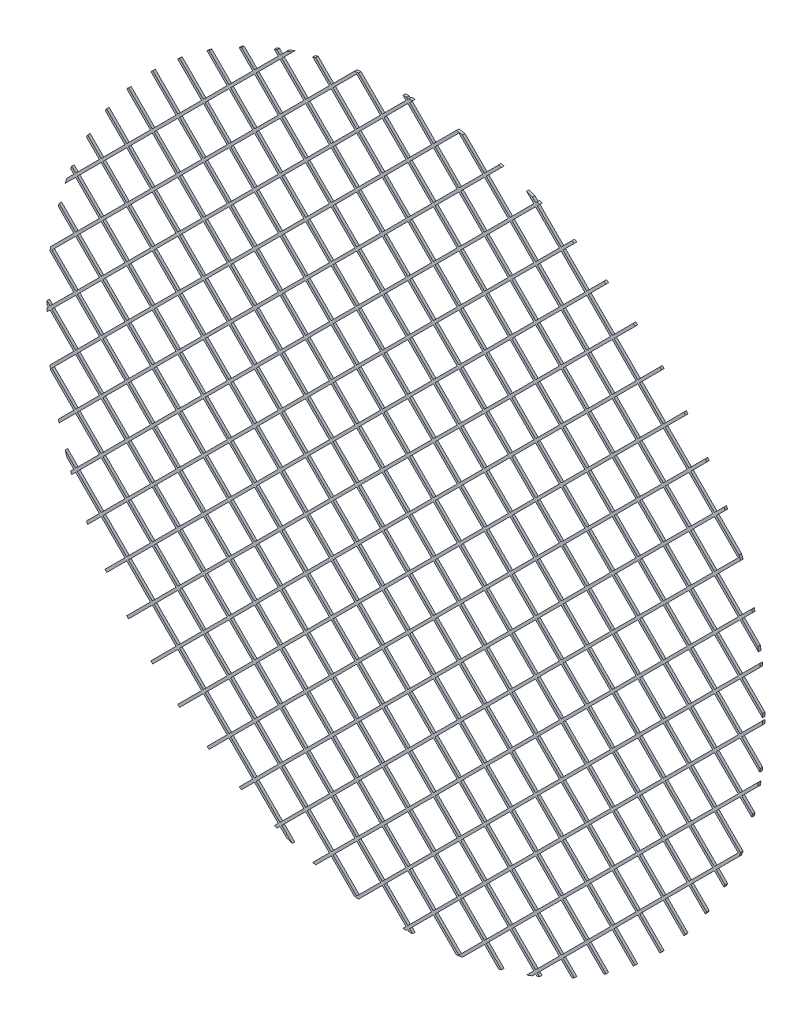
SolidWorks part; units mm, degrees
ref_plane "Front Plane" through (0, 0, 0) normal (0, 0, 1) x (1, 0, 0)
ref_plane "Top Plane" through (0, 0, 0) normal (0, 1, 0) x (1, 0, 0)
ref_plane "Right Plane" through (0, 0, 0) normal (1, 0, 0) x (0, 0, -1)
sketch "Sketch1" plane through (0, 0, 0) normal (0, 0, 1) x (1, 0, 0)
  line L202 (6.9999, -0.034) -> (6.5602, 0.4057)
  line L204 (6.9999, 0.0368) -> (6.5956, 0.4411)
  line L212 (6.9217, 1.0443) -> (6.5602, 1.4057)
  line L214 (6.9085, 1.1282) -> (6.5956, 1.4411)
  line L224 (6.5394, 2.4973) -> (6.0956, 2.9411)
  line L584 (-2.4398, 6.4764) -> (-2.3075, 6.6087)
  line L585 (-6.9302, 0.986) -> (-6.4751, 1.4411)
  line L587 (-2.4044, 6.4411) -> (-2.2003, 6.6452)
  line L590 (-6.6087, 2.3075) -> (-6.4751, 2.4411)
  line L592 (-6.6452, 2.2003) -> (-6.4398, 2.4057)
  line L596 (-5.439, 4.4065) -> (-5.4044, 4.4411)
  line L612 (-2.4398, 6.4764) -> (-2.5012, 6.5379)
  line L613 (-2.4751, 6.4411) -> (-2.5522, 6.5181)
  line L614 (-2.9398, 5.9764) -> (-2.4751, 6.4411)
  line L615 (-2.9044, 5.9411) -> (-2.4398, 6.4057)
  line L616 (-2.9398, 5.9764) -> (-3.1928, 6.2295)
  line L617 (-2.9751, 5.9411) -> (-3.2394, 6.2053)
  line L618 (-1.4398, 6.4764) -> (-0.986, 6.9302)
  line L619 (-1.4044, 6.4411) -> (-0.9398, 6.9057)
  line L620 (-1.4398, 6.4764) -> (-1.7429, 6.7796)
  line L621 (-1.4751, 6.4411) -> (-1.7989, 6.7649)
  line L622 (-0.9044, 6.9411) -> (-0.9041, 6.9414)
  line L623 (-0.4398, 6.4764) -> (0.0249, 6.9411)
  line L624 (-0.4044, 6.4411) -> (0.0602, 6.9057)
  line L625 (-0.4398, 6.4764) -> (-0.9046, 6.9413)
  line L626 (-0.4751, 6.4411) -> (-0.9398, 6.9057)
  line L627 (0.0602, 6.9764) -> (0.0833, 6.9995)
  line L628 (0.0956, 6.9411) -> (0.1528, 6.9983)
  line L629 (0.0602, 6.9764) -> (0.0368, 6.9999)
  line L630 (0.0249, 6.9411) -> (-0.034, 6.9999)
  line L631 (2.5602, 6.4764) -> (2.5879, 6.5041)
  line L632 (2.5956, 6.4411) -> (2.6383, 6.4838)
  line L633 (2.5602, 6.4764) -> (2.4973, 6.5394)
  line L634 (2.5249, 6.4411) -> (2.3846, 6.5813)
  line L635 (1.5602, 6.4764) -> (1.8381, 6.7544)
  line L636 (1.5956, 6.4411) -> (1.8935, 6.739)
  line L637 (1.5602, 6.4764) -> (1.1282, 6.9085)
  line L638 (1.5249, 6.4411) -> (1.0602, 6.9057)
  line L639 (0.5602, 6.4764) -> (1.0105, 6.9267)
  line L640 (0.5956, 6.4411) -> (1.0602, 6.9057)
  line L641 (0.5602, 6.4764) -> (0.0956, 6.9411)
  line L642 (0.5249, 6.4411) -> (0.0602, 6.9057)
  line L643 (-1.9398, 5.9764) -> (-1.4751, 6.4411)
  line L644 (-1.9044, 5.9411) -> (-1.4398, 6.4057)
  line L645 (-1.9398, 5.9764) -> (-2.4044, 6.4411)
  line L646 (-1.9751, 5.9411) -> (-2.4398, 6.4057)
  line L647 (-0.9398, 5.9764) -> (-0.4751, 6.4411)
  line L648 (-0.9044, 5.9411) -> (-0.4398, 6.4057)
  line L649 (-0.9398, 5.9764) -> (-1.4044, 6.4411)
  line L650 (-0.9751, 5.9411) -> (-1.4398, 6.4057)
  line L651 (0.0602, 5.9764) -> (0.5249, 6.4411)
  line L652 (0.0956, 5.9411) -> (0.5602, 6.4057)
  line L653 (0.0602, 5.9764) -> (-0.4044, 6.4411)
  line L654 (0.0249, 5.9411) -> (-0.4398, 6.4057)
  line L655 (1.0602, 5.9764) -> (1.5249, 6.4411)
  line L656 (1.0956, 5.9411) -> (1.5602, 6.4057)
  line L657 (1.0602, 5.9764) -> (0.5956, 6.4411)
  line L658 (1.0249, 5.9411) -> (0.5602, 6.4057)
  line L659 (2.0602, 5.9764) -> (2.5249, 6.4411)
  line L660 (2.0956, 5.9411) -> (2.5602, 6.4057)
  line L661 (2.0602, 5.9764) -> (1.5956, 6.4411)
  line L662 (2.0249, 5.9411) -> (1.5602, 6.4057)
  line L663 (3.0602, 5.9764) -> (3.272, 6.1882)
  line L664 (3.0956, 5.9411) -> (3.3181, 6.1636)
  line L665 (3.0602, 5.9764) -> (2.5956, 6.4411)
  line L666 (3.0249, 5.9411) -> (2.5602, 6.4057)
  line L667 (-3.4398, 5.4764) -> (-2.9751, 5.9411)
  line L668 (-3.4044, 5.4411) -> (-2.9398, 5.9057)
  line L669 (-3.4398, 5.4764) -> (-3.8255, 5.8622)
  line L670 (-3.4751, 5.4411) -> (-3.8682, 5.8341)
  line L671 (-2.4398, 5.4764) -> (-1.9751, 5.9411)
  line L672 (-2.4044, 5.4411) -> (-1.9398, 5.9057)
  line L673 (-2.4398, 5.4764) -> (-2.9044, 5.9411)
  line L674 (-2.4751, 5.4411) -> (-2.9398, 5.9057)
  line L675 (-1.4398, 5.4764) -> (-0.9751, 5.9411)
  line L676 (-1.4044, 5.4411) -> (-0.9398, 5.9057)
  line L677 (-1.4398, 5.4764) -> (-1.9044, 5.9411)
  line L678 (-1.4751, 5.4411) -> (-1.9398, 5.9057)
  line L679 (-0.4398, 5.4764) -> (0.0249, 5.9411)
  line L680 (-0.4044, 5.4411) -> (0.0602, 5.9057)
  line L681 (-0.4398, 5.4764) -> (-0.9044, 5.9411)
  line L682 (-0.4751, 5.4411) -> (-0.9398, 5.9057)
  line L683 (0.5602, 5.4764) -> (1.0249, 5.9411)
  line L684 (0.5956, 5.4411) -> (1.0602, 5.9057)
  line L685 (0.5602, 5.4764) -> (0.0956, 5.9411)
  line L686 (0.5249, 5.4411) -> (0.0602, 5.9057)
  line L687 (1.5602, 5.4764) -> (2.0249, 5.9411)
  line L688 (1.5956, 5.4411) -> (2.0602, 5.9057)
  line L689 (1.5602, 5.4764) -> (1.0956, 5.9411)
  line L690 (1.5249, 5.4411) -> (1.0602, 5.9057)
  line L691 (2.5602, 5.4764) -> (3.0249, 5.9411)
  line L692 (2.5956, 5.4411) -> (3.0602, 5.9057)
  line L693 (2.5602, 5.4764) -> (2.0956, 5.9411)
  line L694 (2.5249, 5.4411) -> (2.0602, 5.9057)
  line L695 (3.5602, 5.4764) -> (3.898, 5.8142)
  line L696 (3.5956, 5.4411) -> (3.9402, 5.7857)
  line L697 (3.5602, 5.4764) -> (3.0956, 5.9411)
  line L698 (3.5249, 5.4411) -> (3.0602, 5.9057)
  line L699 (4.0602, 4.9764) -> (4.4704, 5.3866)
  line L700 (4.0956, 4.9411) -> (4.5089, 5.3544)
  line L701 (4.0602, 4.9764) -> (3.5956, 5.4411)
  line L702 (4.0249, 4.9411) -> (3.5602, 5.4057)
  line L703 (3.0602, 4.9764) -> (2.5956, 5.4411)
  line L704 (3.0249, 4.9411) -> (2.5602, 5.4057)
  line L705 (3.0602, 4.9764) -> (3.5249, 5.4411)
  line L706 (3.0956, 4.9411) -> (3.5602, 5.4057)
  line L707 (2.0602, 4.9764) -> (2.5249, 5.4411)
  line L708 (2.0956, 4.9411) -> (2.5602, 5.4057)
  line L709 (2.0602, 4.9764) -> (1.5956, 5.4411)
  line L710 (2.0249, 4.9411) -> (1.5602, 5.4057)
  line L711 (1.0602, 4.9764) -> (1.5249, 5.4411)
  line L712 (1.0956, 4.9411) -> (1.5602, 5.4057)
  line L713 (1.0602, 4.9764) -> (0.5956, 5.4411)
  line L714 (1.0249, 4.9411) -> (0.5602, 5.4057)
  line L715 (0.0602, 4.9764) -> (0.5249, 5.4411)
  line L716 (0.0956, 4.9411) -> (0.5602, 5.4057)
  line L717 (0.0602, 4.9764) -> (-0.4044, 5.4411)
  line L718 (0.0249, 4.9411) -> (-0.4398, 5.4057)
  line L719 (-0.9398, 4.9764) -> (-0.4751, 5.4411)
  line L720 (-0.9044, 4.9411) -> (-0.4398, 5.4057)
  line L721 (-0.9398, 4.9764) -> (-1.4044, 5.4411)
  line L722 (-0.9751, 4.9411) -> (-1.4398, 5.4057)
  line L723 (-1.9398, 4.9764) -> (-1.4751, 5.4411)
  line L724 (-1.9044, 4.9411) -> (-1.4398, 5.4057)
  line L725 (-1.9398, 4.9764) -> (-2.4044, 5.4411)
  line L726 (-1.9751, 4.9411) -> (-2.4398, 5.4057)
  line L727 (-2.9398, 4.9764) -> (-2.4751, 5.4411)
  line L728 (-2.9044, 4.9411) -> (-2.4398, 5.4057)
  line L729 (-2.9398, 4.9764) -> (-3.4044, 5.4411)
  line L730 (-2.9751, 4.9411) -> (-3.4398, 5.4057)
  line L731 (-3.9398, 4.9764) -> (-3.4751, 5.4411)
  line L732 (-3.9044, 4.9411) -> (-3.4398, 5.4057)
  line L733 (-3.9398, 4.9764) -> (-4.4042, 5.4409)
  line L734 (-3.9751, 4.9411) -> (-4.4432, 5.4091)
  line L735 (-4.4398, 4.4764) -> (-3.9751, 4.9411)
  line L736 (-4.4044, 4.4411) -> (-3.9398, 4.9057)
  line L737 (-4.4398, 4.4764) -> (-4.9314, 4.968)
  line L738 (-4.4751, 4.4411) -> (-4.9667, 4.9327)
  line L739 (-3.4398, 4.4764) -> (-2.9751, 4.9411)
  line L740 (-3.4044, 4.4411) -> (-2.9398, 4.9057)
  line L741 (-3.4398, 4.4764) -> (-3.9044, 4.9411)
  line L742 (-3.4751, 4.4411) -> (-3.9398, 4.9057)
  line L743 (-2.4398, 4.4764) -> (-1.9751, 4.9411)
  line L744 (-2.4044, 4.4411) -> (-1.9398, 4.9057)
  line L745 (-2.4398, 4.4764) -> (-2.9044, 4.9411)
  line L746 (-2.4751, 4.4411) -> (-2.9398, 4.9057)
  line L747 (-1.4398, 4.4764) -> (-0.9751, 4.9411)
  line L748 (-1.4044, 4.4411) -> (-0.9398, 4.9057)
  line L749 (-1.4398, 4.4764) -> (-1.9044, 4.9411)
  line L750 (-1.4751, 4.4411) -> (-1.9398, 4.9057)
  line L751 (-0.4398, 4.4764) -> (0.0249, 4.9411)
  line L752 (-0.4044, 4.4411) -> (0.0602, 4.9057)
  line L753 (-0.4398, 4.4764) -> (-0.9044, 4.9411)
  line L754 (-0.4751, 4.4411) -> (-0.9398, 4.9057)
  line L755 (0.5602, 4.4764) -> (1.0249, 4.9411)
  line L756 (0.5956, 4.4411) -> (1.0602, 4.9057)
  line L757 (0.5602, 4.4764) -> (0.0956, 4.9411)
  line L758 (0.5249, 4.4411) -> (0.0602, 4.9057)
  line L759 (1.5602, 4.4764) -> (2.0249, 4.9411)
  line L760 (1.5956, 4.4411) -> (2.0602, 4.9057)
  line L761 (1.5602, 4.4764) -> (1.0956, 4.9411)
  line L762 (1.5249, 4.4411) -> (1.0602, 4.9057)
  line L763 (2.5602, 4.4764) -> (3.0249, 4.9411)
  line L764 (2.5956, 4.4411) -> (3.0602, 4.9057)
  line L765 (2.5602, 4.4764) -> (2.0956, 4.9411)
  line L766 (2.5249, 4.4411) -> (2.0602, 4.9057)
  line L767 (3.5602, 4.4764) -> (4.0249, 4.9411)
  line L768 (3.5956, 4.4411) -> (4.0602, 4.9057)
  line L769 (3.5602, 4.4764) -> (3.0956, 4.9411)
  line L770 (3.5249, 4.4411) -> (3.0602, 4.9057)
  line L771 (4.5602, 4.4764) -> (4.9915, 4.9077)
  line L772 (4.5956, 4.4411) -> (5.0264, 4.8719)
  line L773 (4.5602, 4.4764) -> (4.0956, 4.9411)
  line L774 (4.5249, 4.4411) -> (4.0602, 4.9057)
  line L775 (-4.9398, 3.9764) -> (-4.4751, 4.4411)
  line L776 (-4.9044, 3.9411) -> (-4.4398, 4.4057)
  line L777 (-4.9398, 3.9764) -> (-5.4079, 4.4446)
  line L778 (-4.9751, 3.9411) -> (-5.4397, 4.4056)
  line L779 (-3.9398, 3.9764) -> (-3.4751, 4.4411)
  line L780 (-3.9044, 3.9411) -> (-3.4398, 4.4057)
  line L781 (-3.9398, 3.9764) -> (-4.4044, 4.4411)
  line L782 (-3.9751, 3.9411) -> (-4.4398, 4.4057)
  line L783 (-2.9398, 3.9764) -> (-2.4751, 4.4411)
  line L784 (-2.9044, 3.9411) -> (-2.4398, 4.4057)
  line L785 (-2.9398, 3.9764) -> (-3.4044, 4.4411)
  line L786 (-2.9751, 3.9411) -> (-3.4398, 4.4057)
  line L787 (-1.9398, 3.9764) -> (-1.4751, 4.4411)
  line L788 (-1.9044, 3.9411) -> (-1.4398, 4.4057)
  line L789 (-1.9398, 3.9764) -> (-2.4044, 4.4411)
  line L790 (-1.9751, 3.9411) -> (-2.4398, 4.4057)
  line L791 (-0.9398, 3.9764) -> (-0.4751, 4.4411)
  line L792 (-0.9044, 3.9411) -> (-0.4398, 4.4057)
  line L793 (-0.9398, 3.9764) -> (-1.4044, 4.4411)
  line L794 (-0.9751, 3.9411) -> (-1.4398, 4.4057)
  line L795 (0.0602, 3.9764) -> (0.5249, 4.4411)
  line L796 (0.0956, 3.9411) -> (0.5602, 4.4057)
  line L797 (0.0602, 3.9764) -> (-0.4044, 4.4411)
  line L798 (0.0249, 3.9411) -> (-0.4398, 4.4057)
  line L799 (1.0602, 3.9764) -> (1.5249, 4.4411)
  line L800 (1.0956, 3.9411) -> (1.5602, 4.4057)
  line L801 (1.0249, 3.9411) -> (0.5602, 4.4057)
  line L802 (1.0602, 3.9764) -> (0.5956, 4.4411)
  line L803 (2.0602, 3.9764) -> (2.5249, 4.4411)
  line L804 (2.0956, 3.9411) -> (2.5602, 4.4057)
  line L805 (2.0602, 3.9764) -> (1.5956, 4.4411)
  line L806 (2.0249, 3.9411) -> (1.5602, 4.4057)
  line L807 (3.0602, 3.9764) -> (3.5249, 4.4411)
  line L808 (3.0956, 3.9411) -> (3.5602, 4.4057)
  line L809 (3.0602, 3.9764) -> (2.5956, 4.4411)
  line L810 (3.0249, 3.9411) -> (2.5602, 4.4057)
  line L811 (4.0602, 3.9764) -> (4.5249, 4.4411)
  line L812 (4.0956, 3.9411) -> (4.5602, 4.4057)
  line L813 (4.0602, 3.9764) -> (3.5956, 4.4411)
  line L814 (4.0249, 3.9411) -> (3.5602, 4.4057)
  line L815 (5.0602, 3.9764) -> (5.4619, 4.3781)
  line L816 (5.0956, 3.9411) -> (5.4932, 4.3387)
  line L817 (5.0602, 3.9764) -> (4.5956, 4.4411)
  line L818 (5.0249, 3.9411) -> (4.5602, 4.4057)
  line L819 (5.5602, 3.4764) -> (5.8807, 3.797)
  line L820 (5.5956, 3.4411) -> (5.9083, 3.7539)
  line L821 (5.5602, 3.4764) -> (5.0956, 3.9411)
  line L822 (5.5249, 3.4411) -> (5.0602, 3.9057)
  line L823 (4.5602, 3.4764) -> (5.0249, 3.9411)
  line L824 (4.5956, 3.4411) -> (5.0602, 3.9057)
  line L825 (4.5602, 3.4764) -> (4.0956, 3.9411)
  line L826 (4.5249, 3.4411) -> (4.0602, 3.9057)
  line L827 (3.5602, 3.4764) -> (4.0249, 3.9411)
  line L828 (3.5956, 3.4411) -> (4.0602, 3.9057)
  line L829 (3.5602, 3.4764) -> (3.0956, 3.9411)
  line L830 (3.5249, 3.4411) -> (3.0602, 3.9057)
  line L831 (2.5602, 3.4764) -> (3.0249, 3.9411)
  line L832 (2.5956, 3.4411) -> (3.0602, 3.9057)
  line L833 (2.5249, 3.4411) -> (2.0602, 3.9057)
  line L834 (2.5602, 3.4764) -> (2.0956, 3.9411)
  line L835 (1.5602, 3.4764) -> (2.0249, 3.9411)
  line L836 (1.5956, 3.4411) -> (2.0602, 3.9057)
  line L837 (1.5249, 3.4411) -> (1.0602, 3.9057)
  line L838 (1.5602, 3.4764) -> (1.0956, 3.9411)
  line L839 (0.5602, 3.4764) -> (1.0249, 3.9411)
  line L840 (0.5956, 3.4411) -> (1.0602, 3.9057)
  line L841 (0.5249, 3.4411) -> (0.0602, 3.9057)
  line L842 (0.5602, 3.4764) -> (0.0956, 3.9411)
  line L843 (-0.4398, 3.4764) -> (0.0249, 3.9411)
  line L844 (-0.4044, 3.4411) -> (0.0602, 3.9057)
  line L845 (-0.4398, 3.4764) -> (-0.9044, 3.9411)
  line L846 (-0.4751, 3.4411) -> (-0.9398, 3.9057)
  line L847 (-1.4398, 3.4764) -> (-0.9751, 3.9411)
  line L848 (-1.4044, 3.4411) -> (-0.9398, 3.9057)
  line L849 (-1.4398, 3.4764) -> (-1.9044, 3.9411)
  line L850 (-1.4751, 3.4411) -> (-1.9398, 3.9057)
  line L851 (-2.4398, 3.4764) -> (-1.9751, 3.9411)
  line L852 (-2.4044, 3.4411) -> (-1.9398, 3.9057)
  line L853 (-2.4751, 3.4411) -> (-2.9398, 3.9057)
  line L854 (-2.4398, 3.4764) -> (-2.9044, 3.9411)
  line L855 (-3.4398, 3.4764) -> (-2.9751, 3.9411)
  line L856 (-3.4044, 3.4411) -> (-2.9398, 3.9057)
  line L857 (-3.4398, 3.4764) -> (-3.9044, 3.9411)
  line L858 (-3.4751, 3.4411) -> (-3.9398, 3.9057)
  line L859 (-4.4398, 3.4764) -> (-3.9751, 3.9411)
  line L860 (-4.4044, 3.4411) -> (-3.9398, 3.9057)
  line L861 (-4.4398, 3.4764) -> (-4.9044, 3.9411)
  line L862 (-4.4751, 3.4411) -> (-4.9398, 3.9057)
  line L863 (-5.4398, 3.4764) -> (-4.9751, 3.9411)
  line L864 (-5.4044, 3.4411) -> (-4.9398, 3.9057)
  line L865 (-5.4398, 3.4764) -> (-5.8331, 3.8698)
  line L866 (-5.4751, 3.4411) -> (-5.8612, 3.8271)
  line L867 (-5.9398, 2.9764) -> (-5.4751, 3.4411)
  line L868 (-5.9044, 2.9411) -> (-5.4398, 3.4057)
  line L869 (-5.9398, 2.9764) -> (-6.2045, 3.2411)
  line L870 (-5.9751, 2.9411) -> (-6.2286, 3.1945)
  line L871 (-4.9398, 2.9764) -> (-4.4751, 3.4411)
  line L872 (-4.9044, 2.9411) -> (-4.4398, 3.4057)
  line L873 (-4.9398, 2.9764) -> (-5.4044, 3.4411)
  line L874 (-4.9751, 2.9411) -> (-5.4398, 3.4057)
  line L875 (-3.9398, 2.9764) -> (-3.4751, 3.4411)
  line L876 (-3.9044, 2.9411) -> (-3.4398, 3.4057)
  line L877 (-3.9398, 2.9764) -> (-4.4044, 3.4411)
  line L878 (-3.9751, 2.9411) -> (-4.4398, 3.4057)
  line L879 (-2.9398, 2.9764) -> (-2.4751, 3.4411)
  line L880 (-2.9044, 2.9411) -> (-2.4398, 3.4057)
  line L881 (-2.9751, 2.9411) -> (-3.4398, 3.4057)
  line L882 (-2.9398, 2.9764) -> (-3.4044, 3.4411)
  line L883 (-1.9398, 2.9764) -> (-1.4751, 3.4411)
  line L884 (-1.9044, 2.9411) -> (-1.4398, 3.4057)
  line L885 (-1.9398, 2.9764) -> (-2.4044, 3.4411)
  line L886 (-1.9751, 2.9411) -> (-2.4398, 3.4057)
  line L887 (-0.9398, 2.9764) -> (-0.4751, 3.4411)
  line L888 (-0.9044, 2.9411) -> (-0.4398, 3.4057)
  line L889 (-0.9751, 2.9411) -> (-1.4398, 3.4057)
  line L890 (-0.9398, 2.9764) -> (-1.4044, 3.4411)
  line L891 (0.0602, 2.9764) -> (0.5249, 3.4411)
  line L892 (0.0956, 2.9411) -> (0.5602, 3.4057)
  line L893 (0.0602, 2.9764) -> (-0.4044, 3.4411)
  line L894 (0.0249, 2.9411) -> (-0.4398, 3.4057)
  line L895 (1.0602, 2.9764) -> (1.5249, 3.4411)
  line L896 (1.0956, 2.9411) -> (1.5602, 3.4057)
  line L897 (1.0249, 2.9411) -> (0.5602, 3.4057)
  line L898 (1.0602, 2.9764) -> (0.5956, 3.4411)
  line L899 (2.0602, 2.9764) -> (2.5249, 3.4411)
  line L900 (2.0956, 2.9411) -> (2.5602, 3.4057)
  line L901 (2.0602, 2.9764) -> (1.5956, 3.4411)
  line L902 (2.0249, 2.9411) -> (1.5602, 3.4057)
  line L903 (3.0602, 2.9764) -> (3.5249, 3.4411)
  line L904 (3.0249, 2.9411) -> (2.5602, 3.4057)
  line L905 (3.0956, 2.9411) -> (3.5602, 3.4057)
  line L906 (3.0602, 2.9764) -> (2.5956, 3.4411)
  line L907 (4.0602, 2.9764) -> (4.5249, 3.4411)
  line L908 (4.0956, 2.9411) -> (4.5602, 3.4057)
  line L909 (4.0249, 2.9411) -> (3.5602, 3.4057)
  line L910 (4.0602, 2.9764) -> (3.5956, 3.4411)
  line L911 (5.0602, 2.9764) -> (5.5249, 3.4411)
  line L912 (5.0956, 2.9411) -> (5.5602, 3.4057)
  line L913 (5.0249, 2.9411) -> (4.5602, 3.4057)
  line L914 (5.0602, 2.9764) -> (4.5956, 3.4411)
  line L915 (6.0602, 2.9764) -> (6.2454, 3.1616)
  line L916 (6.0956, 2.9411) -> (6.269, 3.1145)
  line L917 (6.0602, 2.9764) -> (5.5956, 3.4411)
  line L918 (6.0249, 2.9411) -> (5.5602, 3.4057)
  line L919 (6.5249, 2.4411) -> (6.0602, 2.9057)
  line L920 (5.5602, 2.4764) -> (6.0249, 2.9411)
  line L921 (5.5956, 2.4411) -> (6.0602, 2.9057)
  line L922 (5.5602, 2.4764) -> (5.0956, 2.9411)
  line L923 (5.5249, 2.4411) -> (5.0602, 2.9057)
  line L924 (4.5602, 2.4764) -> (5.0249, 2.9411)
  line L925 (4.5956, 2.4411) -> (5.0602, 2.9057)
  line L926 (4.5249, 2.4411) -> (4.0602, 2.9057)
  line L927 (4.5602, 2.4764) -> (4.0956, 2.9411)
  line L928 (3.5602, 2.4764) -> (4.0249, 2.9411)
  line L929 (3.5956, 2.4411) -> (4.0602, 2.9057)
  line L930 (3.5249, 2.4411) -> (3.0602, 2.9057)
  line L931 (3.5602, 2.4764) -> (3.0956, 2.9411)
  line L932 (2.5602, 2.4764) -> (3.0249, 2.9411)
  line L933 (2.5956, 2.4411) -> (3.0602, 2.9057)
  line L934 (2.5602, 2.4764) -> (2.0956, 2.9411)
  line L935 (2.5249, 2.4411) -> (2.0602, 2.9057)
  line L936 (1.5602, 2.4764) -> (2.0249, 2.9411)
  line L937 (1.5956, 2.4411) -> (2.0602, 2.9057)
  line L938 (1.5602, 2.4764) -> (1.0956, 2.9411)
  line L939 (1.5249, 2.4411) -> (1.0602, 2.9057)
  line L940 (0.5602, 2.4764) -> (1.0249, 2.9411)
  line L941 (0.5956, 2.4411) -> (1.0602, 2.9057)
  line L942 (0.5249, 2.4411) -> (0.0602, 2.9057)
  line L943 (0.5602, 2.4764) -> (0.0956, 2.9411)
  line L944 (-0.4398, 2.4764) -> (0.0249, 2.9411)
  line L945 (-0.4044, 2.4411) -> (0.0602, 2.9057)
  line L946 (-0.4398, 2.4764) -> (-0.9044, 2.9411)
  line L947 (-0.4751, 2.4411) -> (-0.9398, 2.9057)
  line L948 (-1.4398, 2.4764) -> (-0.9751, 2.9411)
  line L949 (-1.4044, 2.4411) -> (-0.9398, 2.9057)
  line L950 (-1.4751, 2.4411) -> (-1.9398, 2.9057)
  line L951 (-1.4398, 2.4764) -> (-1.9044, 2.9411)
  line L952 (-2.4398, 2.4764) -> (-1.9751, 2.9411)
  line L953 (-2.4044, 2.4411) -> (-1.9398, 2.9057)
  line L954 (-2.4398, 2.4764) -> (-2.9044, 2.9411)
  line L955 (-2.4751, 2.4411) -> (-2.9398, 2.9057)
  line L956 (-3.4398, 2.4764) -> (-2.9751, 2.9411)
  line L957 (-3.4044, 2.4411) -> (-2.9398, 2.9057)
  line L958 (-3.4751, 2.4411) -> (-3.9398, 2.9057)
  line L959 (-3.4398, 2.4764) -> (-3.9044, 2.9411)
  line L960 (-4.4398, 2.4764) -> (-3.9751, 2.9411)
  line L961 (-4.4044, 2.4411) -> (-3.9398, 2.9057)
  line L962 (-4.4398, 2.4764) -> (-4.9044, 2.9411)
  line L963 (-4.4751, 2.4411) -> (-4.9398, 2.9057)
  line L964 (-5.4398, 2.4764) -> (-4.9751, 2.9411)
  line L965 (-5.4044, 2.4411) -> (-4.9398, 2.9057)
  line L966 (-5.4398, 2.4764) -> (-5.9044, 2.9411)
  line L967 (-5.4751, 2.4411) -> (-5.9398, 2.9057)
  line L968 (-6.4044, 2.4411) -> (-5.9398, 2.9057)
  line L969 (-6.4751, 2.4411) -> (-6.5372, 2.5031)
  line L970 (-6.4398, 2.4764) -> (-6.5174, 2.5541)
  line L971 (-6.4398, 2.4764) -> (-5.9751, 2.9411)
  line L972 (-5.9398, 1.9764) -> (-5.4751, 2.4411)
  line L973 (-5.9044, 1.9411) -> (-5.4398, 2.4057)
  line L974 (-5.9751, 1.9411) -> (-6.4398, 2.4057)
  line L975 (-5.9398, 1.9764) -> (-6.4044, 2.4411)
  line L976 (-4.9398, 1.9764) -> (-4.4751, 2.4411)
  line L977 (-4.9044, 1.9411) -> (-4.4398, 2.4057)
  line L978 (-4.9751, 1.9411) -> (-5.4398, 2.4057)
  line L979 (-4.9398, 1.9764) -> (-5.4044, 2.4411)
  line L980 (-3.9398, 1.9764) -> (-3.4751, 2.4411)
  line L981 (-3.9044, 1.9411) -> (-3.4398, 2.4057)
  line L982 (-3.9398, 1.9764) -> (-4.4044, 2.4411)
  line L983 (-3.9751, 1.9411) -> (-4.4398, 2.4057)
  line L984 (-2.9398, 1.9764) -> (-2.4751, 2.4411)
  line L985 (-2.9044, 1.9411) -> (-2.4398, 2.4057)
  line L986 (-2.9398, 1.9764) -> (-3.4044, 2.4411)
  line L987 (-2.9751, 1.9411) -> (-3.4398, 2.4057)
  line L988 (-1.9398, 1.9764) -> (-1.4751, 2.4411)
  line L989 (-1.9044, 1.9411) -> (-1.4398, 2.4057)
  line L990 (-1.9751, 1.9411) -> (-2.4398, 2.4057)
  line L991 (-1.9398, 1.9764) -> (-2.4044, 2.4411)
  line L992 (-0.9398, 1.9764) -> (-0.4751, 2.4411)
  line L993 (-0.9398, 1.9764) -> (-1.4044, 2.4411)
  line L994 (-0.9044, 1.9411) -> (-0.4398, 2.4057)
  line L995 (-0.9751, 1.9411) -> (-1.4398, 2.4057)
  line L996 (0.0602, 1.9764) -> (0.5249, 2.4411)
  line L997 (0.0956, 1.9411) -> (0.5602, 2.4057)
  line L998 (0.0249, 1.9411) -> (-0.4398, 2.4057)
  line L999 (0.0602, 1.9764) -> (-0.4044, 2.4411)
  line L1000 (1.0602, 1.9764) -> (1.5249, 2.4411)
  line L1001 (1.0249, 1.9411) -> (0.5602, 2.4057)
  line L1002 (1.0602, 1.9764) -> (0.5956, 2.4411)
  line L1003 (1.0956, 1.9411) -> (1.5602, 2.4057)
  line L1004 (2.0602, 1.9764) -> (2.5249, 2.4411)
  line L1005 (2.0956, 1.9411) -> (2.5602, 2.4057)
  line L1006 (2.0602, 1.9764) -> (1.5956, 2.4411)
  line L1007 (2.0249, 1.9411) -> (1.5602, 2.4057)
  line L1008 (3.0602, 1.9764) -> (3.5249, 2.4411)
  line L1009 (3.0956, 1.9411) -> (3.5602, 2.4057)
  line L1010 (3.0602, 1.9764) -> (2.5956, 2.4411)
  line L1011 (3.0249, 1.9411) -> (2.5602, 2.4057)
  line L1012 (4.0602, 1.9764) -> (4.5249, 2.4411)
  line L1013 (4.0956, 1.9411) -> (4.5602, 2.4057)
  line L1014 (4.0602, 1.9764) -> (3.5956, 2.4411)
  line L1015 (4.0249, 1.9411) -> (3.5602, 2.4057)
  line L1016 (5.0602, 1.9764) -> (5.5249, 2.4411)
  line L1017 (5.0249, 1.9411) -> (4.5602, 2.4057)
  line L1018 (5.0602, 1.9764) -> (4.5956, 2.4411)
  line L1019 (5.0956, 1.9411) -> (5.5602, 2.4057)
  line L1020 (6.0602, 1.9764) -> (6.5249, 2.4411)
  line L1021 (6.0602, 1.9764) -> (5.5956, 2.4411)
  line L1022 (6.0249, 1.9411) -> (5.5602, 2.4057)
  line L1023 (6.0956, 1.9411) -> (6.57, 2.4155)
  line L1024 (6.5602, 1.4764) -> (6.7891, 1.7053)
  line L1025 (6.5956, 1.4411) -> (6.8031, 1.6486)
  line L1026 (6.5602, 1.4764) -> (6.0956, 1.9411)
  line L1027 (6.5249, 1.4411) -> (6.0602, 1.9057)
  line L1028 (5.5602, 1.4764) -> (6.0249, 1.9411)
  line L1029 (5.5956, 1.4411) -> (6.0602, 1.9057)
  line L1030 (5.5602, 1.4764) -> (5.0956, 1.9411)
  line L1031 (5.5249, 1.4411) -> (5.0602, 1.9057)
  line L1032 (4.5602, 1.4764) -> (5.0249, 1.9411)
  line L1033 (4.5956, 1.4411) -> (5.0602, 1.9057)
  line L1034 (4.5602, 1.4764) -> (4.0956, 1.9411)
  line L1035 (4.5249, 1.4411) -> (4.0602, 1.9057)
  line L1036 (3.5602, 1.4764) -> (4.0249, 1.9411)
  line L1037 (3.5956, 1.4411) -> (4.0602, 1.9057)
  line L1038 (3.5602, 1.4764) -> (3.0956, 1.9411)
  line L1039 (3.5249, 1.4411) -> (3.0602, 1.9057)
  line L1040 (2.5602, 1.4764) -> (3.0249, 1.9411)
  line L1041 (2.5602, 1.4764) -> (2.0956, 1.9411)
  line L1042 (2.5956, 1.4411) -> (3.0602, 1.9057)
  line L1043 (2.5249, 1.4411) -> (2.0602, 1.9057)
  line L1044 (1.5602, 1.4764) -> (1.0956, 1.9411)
  line L1045 (1.5249, 1.4411) -> (1.0602, 1.9057)
  line L1046 (1.5602, 1.4764) -> (2.0249, 1.9411)
  line L1047 (1.5956, 1.4411) -> (2.0602, 1.9057)
  line L1048 (0.5602, 1.4764) -> (0.0956, 1.9411)
  line L1049 (0.5249, 1.4411) -> (0.0602, 1.9057)
  line L1050 (0.5602, 1.4764) -> (1.0249, 1.9411)
  line L1051 (0.5956, 1.4411) -> (1.0602, 1.9057)
  line L1052 (-0.4398, 1.4764) -> (0.0249, 1.9411)
  line L1053 (-0.4044, 1.4411) -> (0.0602, 1.9057)
  line L1054 (-0.4751, 1.4411) -> (-0.9398, 1.9057)
  line L1055 (-0.4398, 1.4764) -> (-0.9044, 1.9411)
  line L1056 (-1.4398, 1.4764) -> (-0.9751, 1.9411)
  line L1057 (-1.4751, 1.4411) -> (-1.9398, 1.9057)
  line L1058 (-1.4398, 1.4764) -> (-1.9044, 1.9411)
  line L1059 (-1.4044, 1.4411) -> (-0.9398, 1.9057)
  line L1060 (-2.4398, 1.4764) -> (-1.9751, 1.9411)
  line L1061 (-2.4044, 1.4411) -> (-1.9398, 1.9057)
  line L1062 (-2.4398, 1.4764) -> (-2.9044, 1.9411)
  line L1063 (-2.4751, 1.4411) -> (-2.9398, 1.9057)
  line L1064 (-3.4398, 1.4764) -> (-2.9751, 1.9411)
  line L1065 (-3.4044, 1.4411) -> (-2.9398, 1.9057)
  line L1066 (-3.4751, 1.4411) -> (-3.9398, 1.9057)
  line L1067 (-3.4398, 1.4764) -> (-3.9044, 1.9411)
  line L1068 (-4.4398, 1.4764) -> (-3.9751, 1.9411)
  line L1069 (-4.4044, 1.4411) -> (-3.9398, 1.9057)
  line L1070 (-4.4398, 1.4764) -> (-4.9044, 1.9411)
  line L1071 (-4.4751, 1.4411) -> (-4.9398, 1.9057)
  line L1072 (-5.4398, 1.4764) -> (-4.9751, 1.9411)
  line L1073 (-5.4044, 1.4411) -> (-4.9398, 1.9057)
  line L1074 (-5.4398, 1.4764) -> (-5.9044, 1.9411)
  line L1075 (-5.4751, 1.4411) -> (-5.9398, 1.9057)
  line L1076 (-6.4398, 1.4764) -> (-5.9751, 1.9411)
  line L1077 (-6.4044, 1.4411) -> (-5.9398, 1.9057)
  line L1078 (-6.4398, 1.4764) -> (-6.7643, 1.801)
  line L1079 (-6.4751, 1.4411) -> (-6.779, 1.745)
  line L1080 (-6.9044, 0.9411) -> (-6.4398, 1.4057)
  line L1082 (-5.9398, 0.9764) -> (-5.4751, 1.4411)
  line L1083 (-5.9044, 0.9411) -> (-5.4398, 1.4057)
  line L1084 (-5.9751, 0.9411) -> (-6.4398, 1.4057)
  line L1085 (-5.9398, 0.9764) -> (-6.4044, 1.4411)
  line L1086 (-4.9398, 0.9764) -> (-4.4751, 1.4411)
  line L1087 (-4.9044, 0.9411) -> (-4.4398, 1.4057)
  line L1088 (-4.9751, 0.9411) -> (-5.4398, 1.4057)
  line L1089 (-4.9398, 0.9764) -> (-5.4044, 1.4411)
  line L1090 (-3.9398, 0.9764) -> (-3.4751, 1.4411)
  line L1091 (-3.9044, 0.9411) -> (-3.4398, 1.4057)
  line L1092 (-3.9751, 0.9411) -> (-4.4398, 1.4057)
  line L1093 (-3.9398, 0.9764) -> (-4.4044, 1.4411)
  line L1094 (-2.9398, 0.9764) -> (-2.4751, 1.4411)
  line L1095 (-2.9044, 0.9411) -> (-2.4398, 1.4057)
  line L1096 (-2.9751, 0.9411) -> (-3.4398, 1.4057)
  line L1097 (-2.9398, 0.9764) -> (-3.4044, 1.4411)
  line L1098 (-1.9398, 0.9764) -> (-1.4751, 1.4411)
  line L1099 (-1.9044, 0.9411) -> (-1.4398, 1.4057)
  line L1100 (-1.9751, 0.9411) -> (-2.4398, 1.4057)
  line L1101 (-1.9398, 0.9764) -> (-2.4044, 1.4411)
  line L1102 (-0.9398, 0.9764) -> (-0.4751, 1.4411)
  line L1103 (-0.9044, 0.9411) -> (-0.4398, 1.4057)
  line L1104 (-0.9751, 0.9411) -> (-1.4398, 1.4057)
  line L1105 (-0.9398, 0.9764) -> (-1.4044, 1.4411)
  line L1106 (0.0602, 0.9764) -> (0.5249, 1.4411)
  line L1107 (0.0956, 0.9411) -> (0.5602, 1.4057)
  line L1108 (0.0249, 0.9411) -> (-0.4398, 1.4057)
  line L1109 (0.0602, 0.9764) -> (-0.4044, 1.4411)
  line L1110 (1.0602, 0.9764) -> (1.5249, 1.4411)
  line L1111 (1.0956, 0.9411) -> (1.5602, 1.4057)
  line L1112 (1.0249, 0.9411) -> (0.5602, 1.4057)
  line L1113 (1.0602, 0.9764) -> (0.5956, 1.4411)
  line L1114 (2.0602, 0.9764) -> (2.5249, 1.4411)
  line L1115 (2.0956, 0.9411) -> (2.5602, 1.4057)
  line L1116 (2.0249, 0.9411) -> (1.5602, 1.4057)
  line L1117 (2.0602, 0.9764) -> (1.5956, 1.4411)
  line L1118 (3.0602, 0.9764) -> (3.5249, 1.4411)
  line L1119 (3.0956, 0.9411) -> (3.5602, 1.4057)
  line L1120 (3.0249, 0.9411) -> (2.5602, 1.4057)
  line L1121 (3.0602, 0.9764) -> (2.5956, 1.4411)
  line L1122 (4.0602, 0.9764) -> (4.5249, 1.4411)
  line L1123 (4.0956, 0.9411) -> (4.5602, 1.4057)
  line L1124 (4.0249, 0.9411) -> (3.5602, 1.4057)
  line L1125 (4.0602, 0.9764) -> (3.5956, 1.4411)
  line L1126 (5.0602, 0.9764) -> (5.5249, 1.4411)
  line L1127 (5.0956, 0.9411) -> (5.5602, 1.4057)
  line L1128 (5.0249, 0.9411) -> (4.5602, 1.4057)
  line L1129 (5.0602, 0.9764) -> (4.5956, 1.4411)
  line L1130 (6.0602, 0.9764) -> (6.5249, 1.4411)
  line L1131 (6.0956, 0.9411) -> (6.5602, 1.4057)
  line L1132 (6.0249, 0.9411) -> (5.5602, 1.4057)
  line L1133 (6.0602, 0.9764) -> (5.5956, 1.4411)
  line L1134 (6.5956, 0.4411) -> (6.9542, 0.7997)
  line L1135 (6.5602, 0.4764) -> (6.9466, 0.8628)
  line L1136 (6.5602, 0.4764) -> (6.0956, 0.9411)
  line L1137 (6.5249, 0.4411) -> (6.0602, 0.9057)
  line L1138 (5.5602, 0.4764) -> (6.0249, 0.9411)
  line L1139 (5.5956, 0.4411) -> (6.0602, 0.9057)
  line L1140 (5.5249, 0.4411) -> (5.0602, 0.9057)
  line L1141 (5.5602, 0.4764) -> (5.0956, 0.9411)
  line L1142 (4.5602, 0.4764) -> (5.0249, 0.9411)
  line L1143 (4.5956, 0.4411) -> (5.0602, 0.9057)
  line L1144 (4.5249, 0.4411) -> (4.0602, 0.9057)
  line L1145 (4.5602, 0.4764) -> (4.0956, 0.9411)
  line L1146 (3.5602, 0.4764) -> (4.0249, 0.9411)
  line L1147 (3.5956, 0.4411) -> (4.0602, 0.9057)
  line L1148 (3.5249, 0.4411) -> (3.0602, 0.9057)
  line L1149 (3.5602, 0.4764) -> (3.0956, 0.9411)
  line L1150 (2.5602, 0.4764) -> (3.0249, 0.9411)
  line L1151 (2.5956, 0.4411) -> (3.0602, 0.9057)
  line L1152 (2.5249, 0.4411) -> (2.0602, 0.9057)
  line L1153 (2.5602, 0.4764) -> (2.0956, 0.9411)
  line L1154 (1.5602, 0.4764) -> (2.0249, 0.9411)
  line L1155 (1.5956, 0.4411) -> (2.0602, 0.9057)
  line L1156 (1.5249, 0.4411) -> (1.0602, 0.9057)
  line L1157 (1.5602, 0.4764) -> (1.0956, 0.9411)
  line L1158 (0.5602, 0.4764) -> (1.0249, 0.9411)
  line L1159 (0.5956, 0.4411) -> (1.0602, 0.9057)
  line L1160 (0.5249, 0.4411) -> (0.0602, 0.9057)
  line L1161 (0.5602, 0.4764) -> (0.0956, 0.9411)
  line L1162 (-0.4398, 0.4764) -> (0.0249, 0.9411)
  line L1163 (-0.4044, 0.4411) -> (0.0602, 0.9057)
  line L1164 (-0.4751, 0.4411) -> (-0.9398, 0.9057)
  line L1165 (-0.4398, 0.4764) -> (-0.9044, 0.9411)
  line L1166 (-1.4398, 0.4764) -> (-0.9751, 0.9411)
  line L1167 (-1.4044, 0.4411) -> (-0.9398, 0.9057)
  line L1168 (-1.4751, 0.4411) -> (-1.9398, 0.9057)
  line L1169 (-1.4398, 0.4764) -> (-1.9044, 0.9411)
  line L1170 (-2.4398, 0.4764) -> (-1.9751, 0.9411)
  line L1171 (-2.4044, 0.4411) -> (-1.9398, 0.9057)
  line L1172 (-2.4751, 0.4411) -> (-2.9398, 0.9057)
  line L1173 (-2.4398, 0.4764) -> (-2.9044, 0.9411)
  line L1174 (-3.4398, 0.4764) -> (-2.9751, 0.9411)
  line L1175 (-3.4044, 0.4411) -> (-2.9398, 0.9057)
  line L1176 (-3.4751, 0.4411) -> (-3.9398, 0.9057)
  line L1177 (-3.4398, 0.4764) -> (-3.9044, 0.9411)
  line L1178 (-4.4398, 0.4764) -> (-3.9751, 0.9411)
  line L1179 (-4.4044, 0.4411) -> (-3.9398, 0.9057)
  line L1180 (-4.4751, 0.4411) -> (-4.9398, 0.9057)
  line L1181 (-4.4398, 0.4764) -> (-4.9044, 0.9411)
  line L1182 (-5.4398, 0.4764) -> (-4.9751, 0.9411)
  line L1183 (-5.4044, 0.4411) -> (-4.9398, 0.9057)
  line L1184 (-5.4398, 0.4764) -> (-5.9044, 0.9411)
  line L1185 (-5.4751, 0.4411) -> (-5.9398, 0.9057)
  line L1186 (-6.4398, 0.4764) -> (-5.9751, 0.9411)
  line L1187 (-6.4044, 0.4411) -> (-5.9398, 0.9057)
  line L1188 (-6.4398, 0.4764) -> (-6.9044, 0.9411)
  line L1189 (-6.4751, 0.4411) -> (-6.941, 0.9069)
  line L1190 (-6.9044, -0.0589) -> (-6.4398, 0.4057)
  line L1191 (-6.9751, -0.0589) -> (-6.9999, -0.0341)
  line L1192 (-6.9398, -0.0236) -> (-6.4751, 0.4411)
  line L1193 (-6.9398, -0.0236) -> (-6.9999, 0.0366)
  line L1194 (-5.9398, -0.0236) -> (-5.4751, 0.4411)
  line L1195 (-5.9044, -0.0589) -> (-5.4398, 0.4057)
  line L1196 (-5.9751, -0.0589) -> (-6.4398, 0.4057)
  line L1197 (-5.9398, -0.0236) -> (-6.4044, 0.4411)
  line L1198 (-4.9398, -0.0236) -> (-4.4751, 0.4411)
  line L1199 (-4.9044, -0.0589) -> (-4.4398, 0.4057)
  line L1200 (-4.9751, -0.0589) -> (-5.4398, 0.4057)
  line L1201 (-4.9398, -0.0236) -> (-5.4044, 0.4411)
  line L1202 (-3.9398, -0.0236) -> (-3.4751, 0.4411)
  line L1203 (-3.9044, -0.0589) -> (-3.4398, 0.4057)
  line L1204 (-3.9751, -0.0589) -> (-4.4398, 0.4057)
  line L1205 (-3.9398, -0.0236) -> (-4.4044, 0.4411)
  line L1206 (-2.9398, -0.0236) -> (-2.4751, 0.4411)
  line L1207 (-2.9044, -0.0589) -> (-2.4398, 0.4057)
  line L1208 (-2.9751, -0.0589) -> (-3.4398, 0.4057)
  line L1209 (-2.9398, -0.0236) -> (-3.4044, 0.4411)
  line L1210 (-1.9398, -0.0236) -> (-1.4751, 0.4411)
  line L1211 (-1.9044, -0.0589) -> (-1.4398, 0.4057)
  line L1212 (-1.9751, -0.0589) -> (-2.4398, 0.4057)
  line L1213 (-1.9398, -0.0236) -> (-2.4044, 0.4411)
  line L1214 (-0.9398, -0.0236) -> (-0.4751, 0.4411)
  line L1215 (-0.9044, -0.0589) -> (-0.4398, 0.4057)
  line L1216 (-0.9751, -0.0589) -> (-1.4398, 0.4057)
  line L1217 (-0.9398, -0.0236) -> (-1.4044, 0.4411)
  line L1218 (0.0602, -0.0236) -> (0.5249, 0.4411)
  line L1219 (0.0956, -0.0589) -> (0.5602, 0.4057)
  line L1220 (0.0602, -0.0236) -> (-0.4044, 0.4411)
  line L1221 (0.0249, -0.0589) -> (-0.4398, 0.4057)
  line L1222 (1.0602, -0.0236) -> (1.5249, 0.4411)
  line L1223 (1.0956, -0.0589) -> (1.5602, 0.4057)
  line L1224 (1.0602, -0.0236) -> (0.5956, 0.4411)
  line L1225 (1.0249, -0.0589) -> (0.5602, 0.4057)
  line L1226 (2.0602, -0.0236) -> (2.5249, 0.4411)
  line L1227 (2.0956, -0.0589) -> (2.5602, 0.4057)
  line L1228 (2.0249, -0.0589) -> (1.5602, 0.4057)
  line L1229 (2.0602, -0.0236) -> (1.5956, 0.4411)
  line L1230 (3.0602, -0.0236) -> (3.5249, 0.4411)
  line L1231 (3.0602, -0.0236) -> (2.5956, 0.4411)
  line L1232 (3.0956, -0.0589) -> (3.5602, 0.4057)
  line L1233 (3.0249, -0.0589) -> (2.5602, 0.4057)
  line L1234 (4.0602, -0.0236) -> (4.5249, 0.4411)
  line L1235 (4.0602, -0.0236) -> (3.5956, 0.4411)
  line L1236 (4.0956, -0.0589) -> (4.5602, 0.4057)
  line L1237 (4.0249, -0.0589) -> (3.5602, 0.4057)
  line L1238 (5.0602, -0.0236) -> (5.5249, 0.4411)
  line L1239 (5.0602, -0.0236) -> (4.5956, 0.4411)
  line L1240 (5.0956, -0.0589) -> (5.5602, 0.4057)
  line L1241 (5.0249, -0.0589) -> (4.5602, 0.4057)
  line L1242 (6.0602, -0.0236) -> (6.5249, 0.4411)
  line L1243 (6.0602, -0.0236) -> (5.5956, 0.4411)
  line L1244 (6.0956, -0.0589) -> (6.5602, 0.4057)
  line L1245 (6.0249, -0.0589) -> (5.5602, 0.4057)
  line L1246 (-8.6736, -0.0589) -> (8.8647, -0.0589) construction
  line L1247 (6.0249, -0.0589) -> (5.5602, -0.5236)
  line L1248 (6.0956, -0.0589) -> (6.5602, -0.5236)
  line L1249 (6.0602, -0.0943) -> (5.5956, -0.5589)
  line L1250 (6.0602, -0.0943) -> (6.5249, -0.5589)
  line L1251 (5.0249, -0.0589) -> (4.5602, -0.5236)
  line L1252 (5.0956, -0.0589) -> (5.5602, -0.5236)
  line L1253 (5.0602, -0.0943) -> (4.5956, -0.5589)
  line L1254 (5.0602, -0.0943) -> (5.5249, -0.5589)
  line L1255 (4.0249, -0.0589) -> (3.5602, -0.5236)
  line L1256 (4.0956, -0.0589) -> (4.5602, -0.5236)
  line L1257 (4.0602, -0.0943) -> (3.5956, -0.5589)
  line L1258 (4.0602, -0.0943) -> (4.5249, -0.5589)
  line L1259 (3.0249, -0.0589) -> (2.5602, -0.5236)
  line L1260 (3.0956, -0.0589) -> (3.5602, -0.5236)
  line L1261 (3.0602, -0.0943) -> (2.5956, -0.5589)
  line L1262 (3.0602, -0.0943) -> (3.5249, -0.5589)
  line L1263 (2.0602, -0.0943) -> (1.5956, -0.5589)
  line L1264 (2.0249, -0.0589) -> (1.5602, -0.5236)
  line L1265 (2.0956, -0.0589) -> (2.5602, -0.5236)
  line L1266 (2.0602, -0.0943) -> (2.5249, -0.5589)
  line L1267 (1.0249, -0.0589) -> (0.5602, -0.5236)
  line L1268 (1.0602, -0.0943) -> (0.5956, -0.5589)
  line L1269 (1.0956, -0.0589) -> (1.5602, -0.5236)
  line L1270 (1.0602, -0.0943) -> (1.5249, -0.5589)
  line L1271 (0.0249, -0.0589) -> (-0.4398, -0.5236)
  line L1272 (0.0602, -0.0943) -> (-0.4044, -0.5589)
  line L1273 (0.0956, -0.0589) -> (0.5602, -0.5236)
  line L1274 (0.0602, -0.0943) -> (0.5249, -0.5589)
  line L1275 (-0.9398, -0.0943) -> (-1.4044, -0.5589)
  line L1276 (-0.9751, -0.0589) -> (-1.4398, -0.5236)
  line L1277 (-0.9044, -0.0589) -> (-0.4398, -0.5236)
  line L1278 (-0.9398, -0.0943) -> (-0.4751, -0.5589)
  line L1279 (-1.9398, -0.0943) -> (-2.4044, -0.5589)
  line L1280 (-1.9751, -0.0589) -> (-2.4398, -0.5236)
  line L1281 (-1.9044, -0.0589) -> (-1.4398, -0.5236)
  line L1282 (-1.9398, -0.0943) -> (-1.4751, -0.5589)
  line L1283 (-2.9398, -0.0943) -> (-3.4044, -0.5589)
  line L1284 (-2.9751, -0.0589) -> (-3.4398, -0.5236)
  line L1285 (-2.9044, -0.0589) -> (-2.4398, -0.5236)
  line L1286 (-2.9398, -0.0943) -> (-2.4751, -0.5589)
  line L1287 (-3.9398, -0.0943) -> (-4.4044, -0.5589)
  line L1288 (-3.9751, -0.0589) -> (-4.4398, -0.5236)
  line L1289 (-3.9044, -0.0589) -> (-3.4398, -0.5236)
  line L1290 (-3.9398, -0.0943) -> (-3.4751, -0.5589)
  line L1291 (-4.9398, -0.0943) -> (-5.4044, -0.5589)
  line L1292 (-4.9751, -0.0589) -> (-5.4398, -0.5236)
  line L1293 (-4.9044, -0.0589) -> (-4.4398, -0.5236)
  line L1294 (-4.9398, -0.0943) -> (-4.4751, -0.5589)
  line L1295 (-5.9398, -0.0943) -> (-6.4044, -0.5589)
  line L1296 (-5.9751, -0.0589) -> (-6.4398, -0.5236)
  line L1297 (-5.9044, -0.0589) -> (-5.4398, -0.5236)
  line L1298 (-5.9398, -0.0943) -> (-5.4751, -0.5589)
  line L1299 (-6.9398, -0.0943) -> (-6.9999, -0.1544)
  line L1300 (-6.9398, -0.0943) -> (-6.4751, -0.5589)
  line L1301 (-6.9751, -0.0589) -> (-6.9999, -0.0837)
  line L1302 (-6.9044, -0.0589) -> (-6.4398, -0.5236)
  line L1303 (-6.4751, -0.5589) -> (-6.941, -1.0248)
  line L1304 (-6.4398, -0.5943) -> (-6.9044, -1.0589)
  line L1305 (-6.4044, -0.5589) -> (-5.9398, -1.0236)
  line L1306 (-6.4398, -0.5943) -> (-5.9751, -1.0589)
  line L1307 (-5.4751, -0.5589) -> (-5.9398, -1.0236)
  line L1308 (-5.4398, -0.5943) -> (-5.9044, -1.0589)
  line L1309 (-5.4044, -0.5589) -> (-4.9398, -1.0236)
  line L1310 (-5.4398, -0.5943) -> (-4.9751, -1.0589)
  line L1311 (-4.4398, -0.5943) -> (-4.9044, -1.0589)
  line L1312 (-4.4751, -0.5589) -> (-4.9398, -1.0236)
  line L1313 (-4.4044, -0.5589) -> (-3.9398, -1.0236)
  line L1314 (-4.4398, -0.5943) -> (-3.9751, -1.0589)
  line L1315 (-3.4398, -0.5943) -> (-3.9044, -1.0589)
  line L1316 (-3.4751, -0.5589) -> (-3.9398, -1.0236)
  line L1317 (-3.4044, -0.5589) -> (-2.9398, -1.0236)
  line L1318 (-3.4398, -0.5943) -> (-2.9751, -1.0589)
  line L1319 (-2.4398, -0.5943) -> (-2.9044, -1.0589)
  line L1320 (-2.4751, -0.5589) -> (-2.9398, -1.0236)
  line L1321 (-2.4044, -0.5589) -> (-1.9398, -1.0236)
  line L1322 (-2.4398, -0.5943) -> (-1.9751, -1.0589)
  line L1323 (-1.4398, -0.5943) -> (-1.9044, -1.0589)
  line L1324 (-1.4751, -0.5589) -> (-1.9398, -1.0236)
  line L1325 (-1.4044, -0.5589) -> (-0.9398, -1.0236)
  line L1326 (-1.4398, -0.5943) -> (-0.9751, -1.0589)
  line L1327 (-0.4398, -0.5943) -> (-0.9044, -1.0589)
  line L1328 (-0.4751, -0.5589) -> (-0.9398, -1.0236)
  line L1329 (-0.4044, -0.5589) -> (0.0602, -1.0236)
  line L1330 (-0.4398, -0.5943) -> (0.0249, -1.0589)
  line L1331 (0.5602, -0.5943) -> (0.0956, -1.0589)
  line L1332 (0.5249, -0.5589) -> (0.0602, -1.0236)
  line L1333 (0.5956, -0.5589) -> (1.0602, -1.0236)
  line L1334 (0.5602, -0.5943) -> (1.0249, -1.0589)
  line L1335 (1.5602, -0.5943) -> (1.0956, -1.0589)
  line L1336 (1.5249, -0.5589) -> (1.0602, -1.0236)
  line L1337 (1.5956, -0.5589) -> (2.0602, -1.0236)
  line L1338 (1.5602, -0.5943) -> (2.0249, -1.0589)
  line L1339 (2.5602, -0.5943) -> (2.0956, -1.0589)
  line L1340 (2.5249, -0.5589) -> (2.0602, -1.0236)
  line L1341 (2.5956, -0.5589) -> (3.0602, -1.0236)
  line L1342 (2.5602, -0.5943) -> (3.0249, -1.0589)
  line L1343 (3.5602, -0.5943) -> (3.0956, -1.0589)
  line L1344 (3.5249, -0.5589) -> (3.0602, -1.0236)
  line L1345 (3.5956, -0.5589) -> (4.0602, -1.0236)
  line L1346 (3.5602, -0.5943) -> (4.0249, -1.0589)
  line L1347 (4.5602, -0.5943) -> (4.0956, -1.0589)
  line L1348 (4.5249, -0.5589) -> (4.0602, -1.0236)
  line L1349 (4.5956, -0.5589) -> (5.0602, -1.0236)
  line L1350 (4.5602, -0.5943) -> (5.0249, -1.0589)
  line L1351 (5.5602, -0.5943) -> (5.0956, -1.0589)
  line L1352 (5.5249, -0.5589) -> (5.0602, -1.0236)
  line L1353 (5.5956, -0.5589) -> (6.0602, -1.0236)
  line L1354 (5.5602, -0.5943) -> (6.0249, -1.0589)
  line L1355 (6.5249, -0.5589) -> (6.0602, -1.0236)
  line L1356 (6.5602, -0.5943) -> (6.0956, -1.0589)
  line L1357 (6.5602, -0.5943) -> (6.9466, -0.9807)
  line L1358 (6.5956, -0.5589) -> (6.9542, -0.9175)
  line L1359 (6.0602, -1.0943) -> (5.5956, -1.5589)
  line L1360 (6.0249, -1.0589) -> (5.5602, -1.5236)
  line L1361 (6.0956, -1.0589) -> (6.5602, -1.5236)
  line L1362 (6.0602, -1.0943) -> (6.5249, -1.5589)
  line L1363 (5.0602, -1.0943) -> (4.5956, -1.5589)
  line L1364 (5.0249, -1.0589) -> (4.5602, -1.5236)
  line L1365 (5.0956, -1.0589) -> (5.5602, -1.5236)
  line L1366 (5.0602, -1.0943) -> (5.5249, -1.5589)
  line L1367 (4.0602, -1.0943) -> (3.5956, -1.5589)
  line L1368 (4.0249, -1.0589) -> (3.5602, -1.5236)
  line L1369 (4.0956, -1.0589) -> (4.5602, -1.5236)
  line L1370 (4.0602, -1.0943) -> (4.5249, -1.5589)
  line L1371 (3.0602, -1.0943) -> (2.5956, -1.5589)
  line L1372 (3.0249, -1.0589) -> (2.5602, -1.5236)
  line L1373 (3.0956, -1.0589) -> (3.5602, -1.5236)
  line L1374 (3.0602, -1.0943) -> (3.5249, -1.5589)
  line L1375 (2.0602, -1.0943) -> (1.5956, -1.5589)
  line L1376 (2.0249, -1.0589) -> (1.5602, -1.5236)
  line L1377 (2.0956, -1.0589) -> (2.5602, -1.5236)
  line L1378 (2.0602, -1.0943) -> (2.5249, -1.5589)
  line L1379 (1.0602, -1.0943) -> (0.5956, -1.5589)
  line L1380 (1.0249, -1.0589) -> (0.5602, -1.5236)
  line L1381 (1.0956, -1.0589) -> (1.5602, -1.5236)
  line L1382 (1.0602, -1.0943) -> (1.5249, -1.5589)
  line L1383 (0.0602, -1.0943) -> (-0.4044, -1.5589)
  line L1384 (0.0249, -1.0589) -> (-0.4398, -1.5236)
  line L1385 (0.0956, -1.0589) -> (0.5602, -1.5236)
  line L1386 (0.0602, -1.0943) -> (0.5249, -1.5589)
  line L1387 (-0.9398, -1.0943) -> (-1.4044, -1.5589)
  line L1388 (-0.9751, -1.0589) -> (-1.4398, -1.5236)
  line L1389 (-0.9044, -1.0589) -> (-0.4398, -1.5236)
  line L1390 (-0.9398, -1.0943) -> (-0.4751, -1.5589)
  line L1391 (-1.9398, -1.0943) -> (-2.4044, -1.5589)
  line L1392 (-1.9751, -1.0589) -> (-2.4398, -1.5236)
  line L1393 (-1.9044, -1.0589) -> (-1.4398, -1.5236)
  line L1394 (-1.9398, -1.0943) -> (-1.4751, -1.5589)
  line L1395 (-2.9398, -1.0943) -> (-3.4044, -1.5589)
  line L1396 (-2.9751, -1.0589) -> (-3.4398, -1.5236)
  line L1397 (-2.9044, -1.0589) -> (-2.4398, -1.5236)
  line L1398 (-2.9398, -1.0943) -> (-2.4751, -1.5589)
  line L1399 (-3.9398, -1.0943) -> (-4.4044, -1.5589)
  line L1400 (-3.9751, -1.0589) -> (-4.4398, -1.5236)
  line L1401 (-3.9044, -1.0589) -> (-3.4398, -1.5236)
  line L1402 (-3.9398, -1.0943) -> (-3.4751, -1.5589)
  line L1403 (-4.9398, -1.0943) -> (-5.4044, -1.5589)
  line L1404 (-4.9751, -1.0589) -> (-5.4398, -1.5236)
  line L1405 (-4.9044, -1.0589) -> (-4.4398, -1.5236)
  line L1406 (-4.9398, -1.0943) -> (-4.4751, -1.5589)
  line L1407 (-5.9398, -1.0943) -> (-6.4044, -1.5589)
  line L1408 (-5.9751, -1.0589) -> (-6.4398, -1.5236)
  line L1409 (-5.9044, -1.0589) -> (-5.4398, -1.5236)
  line L1410 (-5.9398, -1.0943) -> (-5.4751, -1.5589)
  line L1411 (-6.9044, -1.0589) -> (-6.4398, -1.5236)
  line L1412 (-6.4751, -1.5589) -> (-6.779, -1.8628)
  line L1413 (-6.4398, -1.5943) -> (-6.7643, -1.9188)
  line L1414 (-6.4044, -1.5589) -> (-5.9398, -2.0236)
  line L1415 (-6.4398, -1.5943) -> (-5.9751, -2.0589)
  line L1416 (-5.4751, -1.5589) -> (-5.9398, -2.0236)
  line L1417 (-5.4398, -1.5943) -> (-5.9044, -2.0589)
  line L1418 (-5.4044, -1.5589) -> (-4.9398, -2.0236)
  line L1419 (-5.4398, -1.5943) -> (-4.9751, -2.0589)
  line L1420 (-4.4751, -1.5589) -> (-4.9398, -2.0236)
  line L1421 (-4.4398, -1.5943) -> (-4.9044, -2.0589)
  line L1422 (-4.4044, -1.5589) -> (-3.9398, -2.0236)
  line L1423 (-4.4398, -1.5943) -> (-3.9751, -2.0589)
  line L1424 (-3.4398, -1.5943) -> (-3.9044, -2.0589)
  line L1425 (-3.4751, -1.5589) -> (-3.9398, -2.0236)
  line L1426 (-3.4044, -1.5589) -> (-2.9398, -2.0236)
  line L1427 (-3.4398, -1.5943) -> (-2.9751, -2.0589)
  line L1428 (-2.4751, -1.5589) -> (-2.9398, -2.0236)
  line L1429 (-2.4398, -1.5943) -> (-2.9044, -2.0589)
  line L1430 (-2.4044, -1.5589) -> (-1.9398, -2.0236)
  line L1431 (-2.4398, -1.5943) -> (-1.9751, -2.0589)
  line L1432 (-1.4044, -1.5589) -> (-0.9398, -2.0236)
  line L1433 (-1.4398, -1.5943) -> (-1.9044, -2.0589)
  line L1434 (-1.4751, -1.5589) -> (-1.9398, -2.0236)
  line L1435 (-1.4398, -1.5943) -> (-0.9751, -2.0589)
  line L1436 (-0.4398, -1.5943) -> (-0.9044, -2.0589)
  line L1437 (-0.4751, -1.5589) -> (-0.9398, -2.0236)
  line L1438 (-0.4044, -1.5589) -> (0.0602, -2.0236)
  line L1439 (-0.4398, -1.5943) -> (0.0249, -2.0589)
  line L1440 (0.5956, -1.5589) -> (1.0602, -2.0236)
  line L1441 (0.5602, -1.5943) -> (1.0249, -2.0589)
  line L1442 (0.5249, -1.5589) -> (0.0602, -2.0236)
  line L1443 (0.5602, -1.5943) -> (0.0956, -2.0589)
  line L1444 (1.5956, -1.5589) -> (2.0602, -2.0236)
  line L1445 (1.5602, -1.5943) -> (2.0249, -2.0589)
  line L1446 (1.5249, -1.5589) -> (1.0602, -2.0236)
  line L1447 (1.5602, -1.5943) -> (1.0956, -2.0589)
  line L1448 (2.5249, -1.5589) -> (2.0602, -2.0236)
  line L1449 (2.5956, -1.5589) -> (3.0602, -2.0236)
  line L1450 (2.5602, -1.5943) -> (2.0956, -2.0589)
  line L1451 (2.5602, -1.5943) -> (3.0249, -2.0589)
  line L1452 (3.5249, -1.5589) -> (3.0602, -2.0236)
  line L1453 (3.5602, -1.5943) -> (3.0956, -2.0589)
  line L1454 (3.5956, -1.5589) -> (4.0602, -2.0236)
  line L1455 (3.5602, -1.5943) -> (4.0249, -2.0589)
  line L1456 (4.5249, -1.5589) -> (4.0602, -2.0236)
  line L1457 (4.5602, -1.5943) -> (4.0956, -2.0589)
  line L1458 (4.5956, -1.5589) -> (5.0602, -2.0236)
  line L1459 (4.5602, -1.5943) -> (5.0249, -2.0589)
  line L1460 (5.5249, -1.5589) -> (5.0602, -2.0236)
  line L1461 (5.5602, -1.5943) -> (5.0956, -2.0589)
  line L1462 (5.5956, -1.5589) -> (6.0602, -2.0236)
  line L1463 (5.5602, -1.5943) -> (6.0249, -2.0589)
  line L1464 (6.5249, -1.5589) -> (6.0602, -2.0236)
  line L1465 (6.5602, -1.5943) -> (6.0956, -2.0589)
  line L1466 (6.5956, -1.5589) -> (6.8031, -1.7664)
  line L1467 (6.5602, -1.5943) -> (6.7891, -1.8232)
  line L1468 (6.0956, -2.0589) -> (6.57, -2.5334)
  line L1469 (6.0249, -2.0589) -> (5.5602, -2.5236)
  line L1470 (6.0602, -2.0943) -> (5.5956, -2.5589)
  line L1471 (6.0602, -2.0943) -> (6.5249, -2.5589)
  line L1472 (5.0956, -2.0589) -> (5.5602, -2.5236)
  line L1473 (5.0602, -2.0943) -> (4.5956, -2.5589)
  line L1474 (5.0249, -2.0589) -> (4.5602, -2.5236)
  line L1475 (5.0602, -2.0943) -> (5.5249, -2.5589)
  line L1476 (4.0249, -2.0589) -> (3.5602, -2.5236)
  line L1477 (4.0602, -2.0943) -> (3.5956, -2.5589)
  line L1478 (4.0956, -2.0589) -> (4.5602, -2.5236)
  line L1479 (4.0602, -2.0943) -> (4.5249, -2.5589)
  line L1480 (3.0249, -2.0589) -> (2.5602, -2.5236)
  line L1481 (3.0602, -2.0943) -> (2.5956, -2.5589)
  line L1482 (3.0956, -2.0589) -> (3.5602, -2.5236)
  line L1483 (3.0602, -2.0943) -> (3.5249, -2.5589)
  line L1484 (2.0249, -2.0589) -> (1.5602, -2.5236)
  line L1485 (2.0602, -2.0943) -> (1.5956, -2.5589)
  line L1486 (2.0956, -2.0589) -> (2.5602, -2.5236)
  line L1487 (2.0602, -2.0943) -> (2.5249, -2.5589)
  line L1488 (1.0956, -2.0589) -> (1.5602, -2.5236)
  line L1489 (1.0602, -2.0943) -> (0.5956, -2.5589)
  line L1490 (1.0249, -2.0589) -> (0.5602, -2.5236)
  line L1491 (1.0602, -2.0943) -> (1.5249, -2.5589)
  line L1492 (0.0602, -2.0943) -> (-0.4044, -2.5589)
  line L1493 (0.0249, -2.0589) -> (-0.4398, -2.5236)
  line L1494 (0.0956, -2.0589) -> (0.5602, -2.5236)
  line L1495 (0.0602, -2.0943) -> (0.5249, -2.5589)
  line L1496 (-0.9751, -2.0589) -> (-1.4398, -2.5236)
  line L1497 (-0.9044, -2.0589) -> (-0.4398, -2.5236)
  line L1498 (-0.9398, -2.0943) -> (-1.4044, -2.5589)
  line L1499 (-0.9398, -2.0943) -> (-0.4751, -2.5589)
  line L1500 (-1.9398, -2.0943) -> (-2.4044, -2.5589)
  line L1501 (-1.9751, -2.0589) -> (-2.4398, -2.5236)
  line L1502 (-1.9044, -2.0589) -> (-1.4398, -2.5236)
  line L1503 (-1.9398, -2.0943) -> (-1.4751, -2.5589)
  line L1504 (-2.9751, -2.0589) -> (-3.4398, -2.5236)
  line L1505 (-2.9398, -2.0943) -> (-3.4044, -2.5589)
  line L1506 (-2.9044, -2.0589) -> (-2.4398, -2.5236)
  line L1507 (-2.9398, -2.0943) -> (-2.4751, -2.5589)
  line L1508 (-3.9751, -2.0589) -> (-4.4398, -2.5236)
  line L1509 (-3.9398, -2.0943) -> (-4.4044, -2.5589)
  line L1510 (-3.9044, -2.0589) -> (-3.4398, -2.5236)
  line L1511 (-3.9398, -2.0943) -> (-3.4751, -2.5589)
  line L1512 (-4.9398, -2.0943) -> (-5.4044, -2.5589)
  line L1513 (-4.9751, -2.0589) -> (-5.4398, -2.5236)
  line L1514 (-4.9044, -2.0589) -> (-4.4398, -2.5236)
  line L1515 (-4.9398, -2.0943) -> (-4.4751, -2.5589)
  line L1516 (-5.9398, -2.0943) -> (-6.4044, -2.5589)
  line L1517 (-5.9751, -2.0589) -> (-6.4398, -2.5236)
  line L1518 (-5.9044, -2.0589) -> (-5.4398, -2.5236)
  line L1519 (-5.9398, -2.0943) -> (-5.4751, -2.5589)
  line L1520 (-6.4398, -2.5943) -> (-5.9751, -3.0589)
  line L1521 (-6.4398, -2.5943) -> (-6.5174, -2.6719)
  line L1522 (-6.4751, -2.5589) -> (-6.5372, -2.6209)
  line L1523 (-6.4044, -2.5589) -> (-5.9398, -3.0236)
  line L1524 (-5.4751, -2.5589) -> (-5.9398, -3.0236)
  line L1525 (-5.4398, -2.5943) -> (-5.9044, -3.0589)
  line L1526 (-5.4044, -2.5589) -> (-4.9398, -3.0236)
  line L1527 (-5.4398, -2.5943) -> (-4.9751, -3.0589)
  line L1528 (-4.4751, -2.5589) -> (-4.9398, -3.0236)
  line L1529 (-4.4398, -2.5943) -> (-4.9044, -3.0589)
  line L1530 (-4.4044, -2.5589) -> (-3.9398, -3.0236)
  line L1531 (-4.4398, -2.5943) -> (-3.9751, -3.0589)
  line L1532 (-3.4398, -2.5943) -> (-3.9044, -3.0589)
  line L1533 (-3.4751, -2.5589) -> (-3.9398, -3.0236)
  line L1534 (-3.4044, -2.5589) -> (-2.9398, -3.0236)
  line L1535 (-3.4398, -2.5943) -> (-2.9751, -3.0589)
  line L1536 (-2.4751, -2.5589) -> (-2.9398, -3.0236)
  line L1537 (-2.4398, -2.5943) -> (-2.9044, -3.0589)
  line L1538 (-2.4044, -2.5589) -> (-1.9398, -3.0236)
  line L1539 (-2.4398, -2.5943) -> (-1.9751, -3.0589)
  line L1540 (-1.4398, -2.5943) -> (-1.9044, -3.0589)
  line L1541 (-1.4751, -2.5589) -> (-1.9398, -3.0236)
  line L1542 (-1.4044, -2.5589) -> (-0.9398, -3.0236)
  line L1543 (-1.4398, -2.5943) -> (-0.9751, -3.0589)
  line L1544 (-0.4751, -2.5589) -> (-0.9398, -3.0236)
  line L1545 (-0.4398, -2.5943) -> (-0.9044, -3.0589)
  line L1546 (-0.4044, -2.5589) -> (0.0602, -3.0236)
  line L1547 (-0.4398, -2.5943) -> (0.0249, -3.0589)
  line L1548 (0.5602, -2.5943) -> (0.0956, -3.0589)
  line L1549 (0.5249, -2.5589) -> (0.0602, -3.0236)
  line L1550 (0.5956, -2.5589) -> (1.0602, -3.0236)
  line L1551 (0.5602, -2.5943) -> (1.0249, -3.0589)
  line L1552 (1.5249, -2.5589) -> (1.0602, -3.0236)
  line L1553 (1.5602, -2.5943) -> (1.0956, -3.0589)
  line L1554 (1.5956, -2.5589) -> (2.0602, -3.0236)
  line L1555 (1.5602, -2.5943) -> (2.0249, -3.0589)
  line L1556 (2.5249, -2.5589) -> (2.0602, -3.0236)
  line L1557 (2.5602, -2.5943) -> (2.0956, -3.0589)
  line L1558 (2.5956, -2.5589) -> (3.0602, -3.0236)
  line L1559 (2.5602, -2.5943) -> (3.0249, -3.0589)
  line L1560 (3.5602, -2.5943) -> (3.0956, -3.0589)
  line L1561 (3.5249, -2.5589) -> (3.0602, -3.0236)
  line L1562 (3.5956, -2.5589) -> (4.0602, -3.0236)
  line L1563 (3.5602, -2.5943) -> (4.0249, -3.0589)
  line L1564 (4.5602, -2.5943) -> (4.0956, -3.0589)
  line L1565 (4.5249, -2.5589) -> (4.0602, -3.0236)
  line L1566 (4.5956, -2.5589) -> (5.0602, -3.0236)
  line L1567 (4.5602, -2.5943) -> (5.0249, -3.0589)
  line L1568 (5.5249, -2.5589) -> (5.0602, -3.0236)
  line L1569 (5.5602, -2.5943) -> (5.0956, -3.0589)
  line L1570 (5.5956, -2.5589) -> (6.0602, -3.0236)
  line L1571 (5.5602, -2.5943) -> (6.0249, -3.0589)
  line L1572 (6.5249, -2.5589) -> (6.0602, -3.0236)
  line L1573 (6.0249, -3.0589) -> (5.5602, -3.5236)
  line L1574 (6.0602, -3.0943) -> (5.5956, -3.5589)
  line L1575 (6.0956, -3.0589) -> (6.269, -3.2323)
  line L1576 (6.0602, -3.0943) -> (6.2454, -3.2794)
  line L1577 (5.0602, -3.0943) -> (4.5956, -3.5589)
  line L1578 (5.0249, -3.0589) -> (4.5602, -3.5236)
  line L1579 (5.0956, -3.0589) -> (5.5602, -3.5236)
  line L1580 (5.0602, -3.0943) -> (5.5249, -3.5589)
  line L1581 (4.0602, -3.0943) -> (3.5956, -3.5589)
  line L1582 (4.0249, -3.0589) -> (3.5602, -3.5236)
  line L1583 (4.0956, -3.0589) -> (4.5602, -3.5236)
  line L1584 (4.0602, -3.0943) -> (4.5249, -3.5589)
  line L1585 (3.0602, -3.0943) -> (2.5956, -3.5589)
  line L1586 (3.0956, -3.0589) -> (3.5602, -3.5236)
  line L1587 (3.0249, -3.0589) -> (2.5602, -3.5236)
  line L1588 (3.0602, -3.0943) -> (3.5249, -3.5589)
  line L1589 (2.0249, -3.0589) -> (1.5602, -3.5236)
  line L1590 (2.0602, -3.0943) -> (1.5956, -3.5589)
  line L1591 (2.0956, -3.0589) -> (2.5602, -3.5236)
  line L1592 (2.0602, -3.0943) -> (2.5249, -3.5589)
  line L1593 (1.0602, -3.0943) -> (0.5956, -3.5589)
  line L1594 (1.0249, -3.0589) -> (0.5602, -3.5236)
  line L1595 (1.0956, -3.0589) -> (1.5602, -3.5236)
  line L1596 (1.0602, -3.0943) -> (1.5249, -3.5589)
  line L1597 (0.0249, -3.0589) -> (-0.4398, -3.5236)
  line L1598 (0.0602, -3.0943) -> (-0.4044, -3.5589)
  line L1599 (0.0956, -3.0589) -> (0.5602, -3.5236)
  line L1600 (0.0602, -3.0943) -> (0.5249, -3.5589)
  line L1601 (-0.9398, -3.0943) -> (-1.4044, -3.5589)
  line L1602 (-0.9751, -3.0589) -> (-1.4398, -3.5236)
  line L1603 (-0.9044, -3.0589) -> (-0.4398, -3.5236)
  line L1604 (-0.9398, -3.0943) -> (-0.4751, -3.5589)
  line L1605 (-1.9751, -3.0589) -> (-2.4398, -3.5236)
  line L1606 (-1.9398, -3.0943) -> (-2.4044, -3.5589)
  line L1607 (-1.9044, -3.0589) -> (-1.4398, -3.5236)
  line L1608 (-1.9398, -3.0943) -> (-1.4751, -3.5589)
  line L1609 (-2.9398, -3.0943) -> (-3.4044, -3.5589)
  line L1610 (-2.9751, -3.0589) -> (-3.4398, -3.5236)
  line L1611 (-2.9044, -3.0589) -> (-2.4398, -3.5236)
  line L1612 (-2.9398, -3.0943) -> (-2.4751, -3.5589)
  line L1613 (-3.9751, -3.0589) -> (-4.4398, -3.5236)
  line L1614 (-3.9398, -3.0943) -> (-4.4044, -3.5589)
  line L1615 (-3.9044, -3.0589) -> (-3.4398, -3.5236)
  line L1616 (-3.9398, -3.0943) -> (-3.4751, -3.5589)
  line L1617 (-4.9751, -3.0589) -> (-5.4398, -3.5236)
  line L1618 (-4.9398, -3.0943) -> (-5.4044, -3.5589)
  line L1619 (-4.9044, -3.0589) -> (-4.4398, -3.5236)
  line L1620 (-4.9398, -3.0943) -> (-4.4751, -3.5589)
  line L1621 (-5.9751, -3.0589) -> (-6.2286, -3.3123)
  line L1622 (-5.9398, -3.0943) -> (-6.2045, -3.3589)
  line L1623 (-5.9044, -3.0589) -> (-5.4398, -3.5236)
  line L1624 (-5.9398, -3.0943) -> (-5.4751, -3.5589)
  line L1625 (-5.4751, -3.5589) -> (-5.8612, -3.9449)
  line L1626 (-5.4398, -3.5943) -> (-5.8331, -3.9876)
  line L1627 (-5.4044, -3.5589) -> (-4.9398, -4.0236)
  line L1628 (-5.4398, -3.5943) -> (-4.9751, -4.0589)
  line L1629 (-4.4751, -3.5589) -> (-4.9398, -4.0236)
  line L1630 (-4.4398, -3.5943) -> (-4.9044, -4.0589)
  line L1631 (-4.4044, -3.5589) -> (-3.9398, -4.0236)
  line L1632 (-4.4398, -3.5943) -> (-3.9751, -4.0589)
  line L1633 (-3.4751, -3.5589) -> (-3.9398, -4.0236)
  line L1634 (-3.4398, -3.5943) -> (-3.9044, -4.0589)
  line L1635 (-3.4044, -3.5589) -> (-2.9398, -4.0236)
  line L1636 (-3.4398, -3.5943) -> (-2.9751, -4.0589)
  line L1637 (-2.4398, -3.5943) -> (-2.9044, -4.0589)
  line L1638 (-2.4751, -3.5589) -> (-2.9398, -4.0236)
  line L1639 (-2.4044, -3.5589) -> (-1.9398, -4.0236)
  line L1640 (-2.4398, -3.5943) -> (-1.9751, -4.0589)
  line L1641 (-1.4751, -3.5589) -> (-1.9398, -4.0236)
  line L1642 (-1.4398, -3.5943) -> (-1.9044, -4.0589)
  line L1643 (-1.4044, -3.5589) -> (-0.9398, -4.0236)
  line L1644 (-1.4398, -3.5943) -> (-0.9751, -4.0589)
  line L1645 (-0.4751, -3.5589) -> (-0.9398, -4.0236)
  line L1646 (-0.4398, -3.5943) -> (-0.9044, -4.0589)
  line L1647 (-0.4044, -3.5589) -> (0.0602, -4.0236)
  line L1648 (-0.4398, -3.5943) -> (0.0249, -4.0589)
  line L1649 (0.5602, -3.5943) -> (0.0956, -4.0589)
  line L1650 (0.5249, -3.5589) -> (0.0602, -4.0236)
  line L1651 (0.5956, -3.5589) -> (1.0602, -4.0236)
  line L1652 (0.5602, -3.5943) -> (1.0249, -4.0589)
  line L1653 (1.5602, -3.5943) -> (1.0956, -4.0589)
  line L1654 (1.5249, -3.5589) -> (1.0602, -4.0236)
  line L1655 (1.5956, -3.5589) -> (2.0602, -4.0236)
  line L1656 (1.5602, -3.5943) -> (2.0249, -4.0589)
  line L1657 (2.5602, -3.5943) -> (2.0956, -4.0589)
  line L1658 (2.5249, -3.5589) -> (2.0602, -4.0236)
  line L1659 (2.5956, -3.5589) -> (3.0602, -4.0236)
  line L1660 (2.5602, -3.5943) -> (3.0249, -4.0589)
  line L1661 (3.5249, -3.5589) -> (3.0602, -4.0236)
  line L1662 (3.5602, -3.5943) -> (3.0956, -4.0589)
  line L1663 (3.5956, -3.5589) -> (4.0602, -4.0236)
  line L1664 (3.5602, -3.5943) -> (4.0249, -4.0589)
  line L1665 (4.5249, -3.5589) -> (4.0602, -4.0236)
  line L1666 (4.5602, -3.5943) -> (4.0956, -4.0589)
  line L1667 (4.5956, -3.5589) -> (5.0602, -4.0236)
  line L1668 (4.5602, -3.5943) -> (5.0249, -4.0589)
  line L1669 (5.5249, -3.5589) -> (5.0602, -4.0236)
  line L1670 (5.5602, -3.5943) -> (5.0956, -4.0589)
  line L1671 (5.5956, -3.5589) -> (5.9083, -3.8717)
  line L1672 (5.5602, -3.5943) -> (5.8807, -3.9148)
  line L1673 (5.0249, -4.0589) -> (4.5602, -4.5236)
  line L1674 (5.0602, -4.0943) -> (4.5956, -4.5589)
  line L1675 (5.0956, -4.0589) -> (5.4932, -4.4566)
  line L1676 (5.0602, -4.0943) -> (5.4619, -4.4959)
  line L1677 (4.0249, -4.0589) -> (3.5602, -4.5236)
  line L1678 (4.0602, -4.0943) -> (3.5956, -4.5589)
  line L1679 (4.0956, -4.0589) -> (4.5602, -4.5236)
  line L1680 (4.0602, -4.0943) -> (4.5249, -4.5589)
  line L1681 (3.0249, -4.0589) -> (2.5602, -4.5236)
  line L1682 (3.0602, -4.0943) -> (2.5956, -4.5589)
  line L1683 (3.0956, -4.0589) -> (3.5602, -4.5236)
  line L1684 (3.0602, -4.0943) -> (3.5249, -4.5589)
  line L1685 (2.0249, -4.0589) -> (1.5602, -4.5236)
  line L1686 (2.0602, -4.0943) -> (1.5956, -4.5589)
  line L1687 (2.0956, -4.0589) -> (2.5602, -4.5236)
  line L1688 (2.0602, -4.0943) -> (2.5249, -4.5589)
  line L1689 (1.0602, -4.0943) -> (0.5956, -4.5589)
  line L1690 (1.0249, -4.0589) -> (0.5602, -4.5236)
  line L1691 (1.0956, -4.0589) -> (1.5602, -4.5236)
  line L1692 (1.0602, -4.0943) -> (1.5249, -4.5589)
  line L1693 (0.0249, -4.0589) -> (-0.4398, -4.5236)
  line L1694 (0.0602, -4.0943) -> (-0.4044, -4.5589)
  line L1695 (0.0956, -4.0589) -> (0.5602, -4.5236)
  line L1696 (0.0602, -4.0943) -> (0.5249, -4.5589)
  line L1697 (-0.9751, -4.0589) -> (-1.4398, -4.5236)
  line L1698 (-0.9398, -4.0943) -> (-1.4044, -4.5589)
  line L1699 (-0.9044, -4.0589) -> (-0.4398, -4.5236)
  line L1700 (-0.9398, -4.0943) -> (-0.4751, -4.5589)
  line L1701 (-1.9751, -4.0589) -> (-2.4398, -4.5236)
  line L1702 (-1.9398, -4.0943) -> (-2.4044, -4.5589)
  line L1703 (-1.9044, -4.0589) -> (-1.4398, -4.5236)
  line L1704 (-1.9398, -4.0943) -> (-1.4751, -4.5589)
  line L1705 (-2.9751, -4.0589) -> (-3.4398, -4.5236)
  line L1706 (-2.9398, -4.0943) -> (-3.4044, -4.5589)
  line L1707 (-2.9044, -4.0589) -> (-2.4398, -4.5236)
  line L1708 (-2.9398, -4.0943) -> (-2.4751, -4.5589)
  line L1709 (-3.9751, -4.0589) -> (-4.4398, -4.5236)
  line L1710 (-3.9398, -4.0943) -> (-4.4044, -4.5589)
  line L1711 (-3.9044, -4.0589) -> (-3.4398, -4.5236)
  line L1712 (-3.9398, -4.0943) -> (-3.4751, -4.5589)
  line L1713 (-4.9751, -4.0589) -> (-5.4397, -4.5235)
  line L1714 (-4.9398, -4.0943) -> (-5.4079, -4.5624)
  line L1715 (-4.9044, -4.0589) -> (-4.4398, -4.5236)
  line L1716 (-4.9398, -4.0943) -> (-4.4751, -4.5589)
  line L1717 (4.5249, -4.5589) -> (4.0602, -5.0236)
  line L1718 (4.5602, -4.5943) -> (4.0956, -5.0589)
  line L1719 (4.5956, -4.5589) -> (5.0264, -4.9897)
  line L1720 (4.5602, -4.5943) -> (4.9915, -5.0255)
  line L1721 (3.5249, -4.5589) -> (3.0602, -5.0236)
  line L1722 (3.5602, -4.5943) -> (3.0956, -5.0589)
  line L1723 (3.5956, -4.5589) -> (4.0602, -5.0236)
  line L1724 (3.5602, -4.5943) -> (4.0249, -5.0589)
  line L1725 (2.5249, -4.5589) -> (2.0602, -5.0236)
  line L1726 (2.5602, -4.5943) -> (2.0956, -5.0589)
  line L1727 (2.5956, -4.5589) -> (3.0602, -5.0236)
  line L1728 (2.5602, -4.5943) -> (3.0249, -5.0589)
  line L1729 (1.5249, -4.5589) -> (1.0602, -5.0236)
  line L1730 (1.5602, -4.5943) -> (1.0956, -5.0589)
  line L1731 (1.5956, -4.5589) -> (2.0602, -5.0236)
  line L1732 (1.5602, -4.5943) -> (2.0249, -5.0589)
  line L1733 (0.5249, -4.5589) -> (0.0602, -5.0236)
  line L1734 (0.5602, -4.5943) -> (0.0956, -5.0589)
  line L1735 (0.5956, -4.5589) -> (1.0602, -5.0236)
  line L1736 (0.5602, -4.5943) -> (1.0249, -5.0589)
  line L1737 (-0.4751, -4.5589) -> (-0.9398, -5.0236)
  line L1738 (-0.4398, -4.5943) -> (-0.9044, -5.0589)
  line L1739 (-0.4044, -4.5589) -> (0.0602, -5.0236)
  line L1740 (-0.4398, -4.5943) -> (0.0249, -5.0589)
  line L1741 (-1.4751, -4.5589) -> (-1.9398, -5.0236)
  line L1742 (-1.4398, -4.5943) -> (-1.9044, -5.0589)
  line L1743 (-1.4044, -4.5589) -> (-0.9398, -5.0236)
  line L1744 (-1.4398, -4.5943) -> (-0.9751, -5.0589)
  line L1745 (-2.4751, -4.5589) -> (-2.9398, -5.0236)
  line L1746 (-2.4398, -4.5943) -> (-2.9044, -5.0589)
  line L1747 (-2.4044, -4.5589) -> (-1.9398, -5.0236)
  line L1748 (-2.4398, -4.5943) -> (-1.9751, -5.0589)
  line L1749 (-3.4751, -4.5589) -> (-3.9398, -5.0236)
  line L1750 (-3.4398, -4.5943) -> (-3.9044, -5.0589)
  line L1751 (-3.4044, -4.5589) -> (-2.9398, -5.0236)
  line L1752 (-3.4398, -4.5943) -> (-2.9751, -5.0589)
  line L1753 (-4.4751, -4.5589) -> (-4.9667, -5.0505)
  line L1754 (-4.4398, -4.5943) -> (-4.9314, -5.0859)
  line L1755 (-4.4044, -4.5589) -> (-3.9398, -5.0236)
  line L1756 (-4.4398, -4.5943) -> (-3.9751, -5.0589)
  line L1757 (-3.9751, -5.0589) -> (-4.4432, -5.5269)
  line L1758 (-3.9398, -5.0943) -> (-4.4042, -5.5587)
  line L1759 (-3.9044, -5.0589) -> (-3.4398, -5.5236)
  line L1760 (-3.9398, -5.0943) -> (-3.4751, -5.5589)
  line L1761 (-2.9751, -5.0589) -> (-3.4398, -5.5236)
  line L1762 (-2.9398, -5.0943) -> (-3.4044, -5.5589)
  line L1763 (-2.9044, -5.0589) -> (-2.4398, -5.5236)
  line L1764 (-2.9398, -5.0943) -> (-2.4751, -5.5589)
  line L1765 (-1.9751, -5.0589) -> (-2.4398, -5.5236)
  line L1766 (-1.9398, -5.0943) -> (-2.4044, -5.5589)
  line L1767 (-1.9044, -5.0589) -> (-1.4398, -5.5236)
  line L1768 (-1.9398, -5.0943) -> (-1.4751, -5.5589)
  line L1769 (-0.9751, -5.0589) -> (-1.4398, -5.5236)
  line L1770 (-0.9398, -5.0943) -> (-1.4044, -5.5589)
  line L1771 (-0.9044, -5.0589) -> (-0.4398, -5.5236)
  line L1772 (-0.9398, -5.0943) -> (-0.4751, -5.5589)
  line L1773 (0.0249, -5.0589) -> (-0.4398, -5.5236)
  line L1774 (0.0602, -5.0943) -> (-0.4044, -5.5589)
  line L1775 (0.0956, -5.0589) -> (0.5602, -5.5236)
  line L1776 (0.0602, -5.0943) -> (0.5249, -5.5589)
  line L1777 (1.0249, -5.0589) -> (0.5602, -5.5236)
  line L1778 (1.0602, -5.0943) -> (0.5956, -5.5589)
  line L1779 (1.0956, -5.0589) -> (1.5602, -5.5236)
  line L1780 (1.0602, -5.0943) -> (1.5249, -5.5589)
  line L1781 (2.0249, -5.0589) -> (1.5602, -5.5236)
  line L1782 (2.0602, -5.0943) -> (1.5956, -5.5589)
  line L1783 (2.0956, -5.0589) -> (2.5602, -5.5236)
  line L1784 (2.0602, -5.0943) -> (2.5249, -5.5589)
  line L1785 (3.0956, -5.0589) -> (3.5602, -5.5236)
  line L1786 (3.0602, -5.0943) -> (3.5249, -5.5589)
  line L1787 (3.0249, -5.0589) -> (2.5602, -5.5236)
  line L1788 (3.0602, -5.0943) -> (2.5956, -5.5589)
  line L1789 (4.0249, -5.0589) -> (3.5602, -5.5236)
  line L1790 (4.0602, -5.0943) -> (3.5956, -5.5589)
  line L1791 (4.0956, -5.0589) -> (4.5089, -5.4722)
  line L1792 (4.0602, -5.0943) -> (4.4704, -5.5044)
  line L1793 (3.5249, -5.5589) -> (3.0602, -6.0236)
  line L1794 (3.5602, -5.5943) -> (3.0956, -6.0589)
  line L1795 (3.5956, -5.5589) -> (3.9402, -5.9036)
  line L1796 (3.5602, -5.5943) -> (3.898, -5.9321)
  line L1797 (2.5249, -5.5589) -> (2.0602, -6.0236)
  line L1798 (2.5602, -5.5943) -> (2.0956, -6.0589)
  line L1799 (2.5956, -5.5589) -> (3.0602, -6.0236)
  line L1800 (2.5602, -5.5943) -> (3.0249, -6.0589)
  line L1801 (1.5249, -5.5589) -> (1.0602, -6.0236)
  line L1802 (1.5602, -5.5943) -> (1.0956, -6.0589)
  line L1803 (1.5956, -5.5589) -> (2.0602, -6.0236)
  line L1804 (1.5602, -5.5943) -> (2.0249, -6.0589)
  line L1805 (0.5249, -5.5589) -> (0.0602, -6.0236)
  line L1806 (0.5602, -5.5943) -> (0.0956, -6.0589)
  line L1807 (0.5956, -5.5589) -> (1.0602, -6.0236)
  line L1808 (0.5602, -5.5943) -> (1.0249, -6.0589)
  line L1809 (-0.4751, -5.5589) -> (-0.9398, -6.0236)
  line L1810 (-0.4398, -5.5943) -> (-0.9044, -6.0589)
  line L1811 (-0.4044, -5.5589) -> (0.0602, -6.0236)
  line L1812 (-0.4398, -5.5943) -> (0.0249, -6.0589)
  line L1813 (-1.4751, -5.5589) -> (-1.9398, -6.0236)
  line L1814 (-1.4398, -5.5943) -> (-1.9044, -6.0589)
  line L1815 (-1.4044, -5.5589) -> (-0.9398, -6.0236)
  line L1816 (-1.4398, -5.5943) -> (-0.9751, -6.0589)
  line L1817 (-2.4751, -5.5589) -> (-2.9398, -6.0236)
  line L1818 (-2.4398, -5.5943) -> (-2.9044, -6.0589)
  line L1819 (-2.4044, -5.5589) -> (-1.9398, -6.0236)
  line L1820 (-2.4398, -5.5943) -> (-1.9751, -6.0589)
  line L1821 (-3.4751, -5.5589) -> (-3.8682, -5.952)
  line L1822 (-3.4398, -5.5943) -> (-3.8255, -5.98)
  line L1823 (-3.4044, -5.5589) -> (-2.9398, -6.0236)
  line L1824 (-3.4398, -5.5943) -> (-2.9751, -6.0589)
  line L1825 (3.0249, -6.0589) -> (2.5602, -6.5236)
  line L1826 (3.0602, -6.0943) -> (2.5956, -6.5589)
  line L1827 (3.0956, -6.0589) -> (3.3181, -6.2814)
  line L1828 (3.0602, -6.0943) -> (3.272, -6.3061)
  line L1829 (2.0249, -6.0589) -> (1.5602, -6.5236)
  line L1830 (2.0602, -6.0943) -> (1.5956, -6.5589)
  line L1831 (2.0956, -6.0589) -> (2.5602, -6.5236)
  line L1832 (2.0602, -6.0943) -> (2.5249, -6.5589)
  line L1833 (1.0249, -6.0589) -> (0.5602, -6.5236)
  line L1834 (1.0602, -6.0943) -> (0.5956, -6.5589)
  line L1835 (1.0956, -6.0589) -> (1.5602, -6.5236)
  line L1836 (1.0602, -6.0943) -> (1.5249, -6.5589)
  line L1837 (0.0249, -6.0589) -> (-0.4398, -6.5236)
  line L1838 (0.0602, -6.0943) -> (-0.4044, -6.5589)
  line L1839 (0.0956, -6.0589) -> (0.5602, -6.5236)
  line L1840 (0.0602, -6.0943) -> (0.5249, -6.5589)
  line L1841 (-0.9751, -6.0589) -> (-1.4398, -6.5236)
  line L1842 (-0.9398, -6.0943) -> (-1.4044, -6.5589)
  line L1843 (-0.9044, -6.0589) -> (-0.4398, -6.5236)
  line L1844 (-0.9398, -6.0943) -> (-0.4751, -6.5589)
  line L1845 (-1.9751, -6.0589) -> (-2.4398, -6.5236)
  line L1846 (-1.9398, -6.0943) -> (-2.4044, -6.5589)
  line L1847 (-1.9044, -6.0589) -> (-1.4398, -6.5236)
  line L1848 (-1.9398, -6.0943) -> (-1.4751, -6.5589)
  line L1849 (0.5249, -6.5589) -> (0.0602, -7.0236)
  line L1850 (0.5602, -6.5943) -> (0.0956, -7.0589)
  line L1851 (0.5956, -6.5589) -> (1.0602, -7.0236)
  line L1852 (0.5602, -6.5943) -> (1.0105, -7.0445)
  line L1853 (1.5249, -6.5589) -> (1.0602, -7.0236)
  line L1854 (1.5602, -6.5943) -> (1.1282, -7.0263)
  line L1855 (1.5956, -6.5589) -> (1.8935, -6.8569)
  line L1856 (1.5602, -6.5943) -> (1.8381, -6.8722)
  line L1857 (2.5249, -6.5589) -> (2.3846, -6.6991)
  line L1858 (2.5602, -6.5943) -> (2.4973, -6.6572)
  line L1859 (2.5956, -6.5589) -> (2.6383, -6.6016)
  line L1860 (2.5602, -6.5943) -> (2.5879, -6.6219)
  line L1861 (0.0249, -7.0589) -> (-0.034, -7.1177)
  line L1862 (0.0602, -7.0943) -> (0.0368, -7.1177)
  line L1863 (0.0956, -7.0589) -> (0.1528, -7.1162)
  line L1864 (0.0602, -7.0943) -> (0.0833, -7.1173)
  line L1865 (-0.4751, -6.5589) -> (-0.9398, -7.0236)
  line L1866 (-0.4398, -6.5943) -> (-0.9046, -7.0591)
  line L1867 (-0.4044, -6.5589) -> (0.0602, -7.0236)
  line L1868 (-0.4398, -6.5943) -> (0.0249, -7.0589)
  line L1869 (-0.9044, -7.0589) -> (-0.9041, -7.0592)
  line L1870 (-1.4751, -6.5589) -> (-1.7989, -6.8827)
  line L1871 (-1.4398, -6.5943) -> (-1.7429, -6.8974)
  line L1872 (-1.4044, -6.5589) -> (-0.9398, -7.0236)
  line L1873 (-1.4398, -6.5943) -> (-0.986, -7.048)
  line L1874 (-2.9751, -6.0589) -> (-3.2394, -6.3232)
  line L1875 (-2.9398, -6.0943) -> (-3.1928, -6.3473)
  line L1876 (-2.9044, -6.0589) -> (-2.4398, -6.5236)
  line L1877 (-2.9398, -6.0943) -> (-2.4751, -6.5589)
  line L1878 (-2.4751, -6.5589) -> (-2.5522, -6.636)
  line L1879 (-2.4398, -6.5943) -> (-2.5012, -6.6557)
  line L1880 (-5.439, -4.5244) -> (-5.4044, -4.5589)
  line L1881 (-6.6452, -2.3182) -> (-6.4398, -2.5236)
  line L1882 (-6.6087, -2.4253) -> (-6.4751, -2.5589)
  line L1883 (-2.4044, -6.5589) -> (-2.2003, -6.763)
  line L1884 (-6.9302, -1.1038) -> (-6.4751, -1.5589)
  line L1885 (-2.4398, -6.5943) -> (-2.3075, -6.7266)
  line L1886 (6.5394, -2.6151) -> (6.0956, -3.0589)
  line L1887 (6.9085, -1.246) -> (6.5956, -1.5589)
  line L1888 (6.9217, -1.1621) -> (6.5602, -1.5236)
  line L1889 (6.9999, -0.1546) -> (6.5956, -0.5589)
  line L1890 (6.9999, -0.0839) -> (6.5602, -0.5236)
  arc A0 (-3.1928, 6.2295) -> (-3.2394, 6.2053) centre (0, 0) ccw
  arc A2 (-2.5012, 6.5379) -> (-2.5522, 6.5181) centre (0, 0) ccw
  arc A3 (-2.2003, 6.6452) -> (-2.3075, 6.6087) centre (0, 0) ccw
  arc A4 (-1.7429, 6.7796) -> (-1.7989, 6.7649) centre (0, 0) ccw
  arc A5 (-3.8255, 5.8622) -> (-3.8682, 5.8341) centre (0, 0) ccw
  arc A6 (-0.9041, 6.9414) -> (-0.986, 6.9302) centre (0, 0) ccw
  arc A7 (0.0368, 6.9999) -> (-0.034, 6.9999) centre (0, 0) ccw
  arc A8 (0.1528, 6.9983) -> (0.0833, 6.9995) centre (0, 0) ccw
  arc A9 (1.1282, 6.9085) -> (1.0105, 6.9267) centre (0, 0) ccw
  arc A10 (1.8935, 6.739) -> (1.8381, 6.7544) centre (0, 0) ccw
  arc A11 (2.4973, 6.5394) -> (2.3846, 6.5813) centre (0, 0) ccw
  arc A12 (2.6383, 6.4838) -> (2.5879, 6.5041) centre (0, 0) ccw
  arc A13 (3.3181, 6.1636) -> (3.272, 6.1882) centre (0, 0) ccw
  arc A14 (-4.4042, 5.4409) -> (-4.4432, 5.4091) centre (0, 0) ccw
  arc A15 (-4.9314, 4.968) -> (-4.9667, 4.9327) centre (0, 0) ccw
  arc A16 (-5.4079, 4.4446) -> (-5.4397, 4.4056) centre (0, 0) ccw
  arc A17 (3.9402, 5.7857) -> (3.898, 5.8142) centre (0, 0) ccw
  arc A18 (4.5089, 5.3544) -> (4.4704, 5.3866) centre (0, 0) ccw
  arc A19 (5.0264, 4.8719) -> (4.9915, 4.9077) centre (0, 0) ccw
  arc A20 (-5.8331, 3.8698) -> (-5.8612, 3.8271) centre (0, 0) ccw
  arc A21 (5.4932, 4.3387) -> (5.4619, 4.3781) centre (0, 0) ccw
  arc A22 (5.9083, 3.7539) -> (5.8807, 3.797) centre (0, 0) ccw
  arc A23 (-6.2045, 3.2411) -> (-6.2286, 3.1945) centre (0, 0) ccw
  arc A24 (-6.5174, 2.5541) -> (-6.5372, 2.5031) centre (0, 0) ccw
  arc A25 (6.269, 3.1145) -> (6.2454, 3.1616) centre (0, 0) ccw
  arc A26 (6.57, 2.4155) -> (6.5394, 2.4973) centre (0, 0) ccw
  arc A27 (-6.6087, 2.3075) -> (-6.6452, 2.2003) centre (0, 0) ccw
  arc A28 (-6.7643, 1.801) -> (-6.779, 1.745) centre (0, 0) ccw
  arc A29 (6.8031, 1.6486) -> (6.7891, 1.7053) centre (0, 0) ccw
  arc A30 (-6.9302, 0.986) -> (-6.941, 0.9069) centre (0, 0) ccw
  arc A31 (-6.9999, 0.0366) -> (-6.9999, -0.0341) centre (0, 0) ccw
  arc A32 (6.9217, 1.0443) -> (6.9085, 1.1282) centre (0, 0) ccw
  arc A33 (6.9542, 0.7997) -> (6.9466, 0.8628) centre (0, 0) ccw
  arc A34 (6.9999, -0.0839) -> (6.9999, -0.1546) centre (0, -0.1178) cw
  arc A35 (6.9999, -0.034) -> (6.9999, 0.0368) centre (0, 0) ccw
  arc A36 (6.9542, -0.9175) -> (6.9466, -0.9807) centre (0, -0.1178) cw
  arc A37 (6.9217, -1.1621) -> (6.9085, -1.246) centre (0, -0.1178) cw
  arc A38 (-6.9999, -0.1544) -> (-6.9999, -0.0837) centre (0, -0.1178) cw
  arc A39 (-6.9302, -1.1038) -> (-6.941, -1.0248) centre (0, -0.1178) cw
  arc A40 (6.8031, -1.7664) -> (6.7891, -1.8232) centre (0, -0.1178) cw
  arc A41 (-6.7643, -1.9188) -> (-6.779, -1.8628) centre (0, -0.1178) cw
  arc A42 (-6.6087, -2.4253) -> (-6.6452, -2.3182) centre (0, -0.1178) cw
  arc A43 (6.57, -2.5334) -> (6.5394, -2.6151) centre (0, -0.1178) cw
  arc A44 (6.269, -3.2323) -> (6.2454, -3.2794) centre (0, -0.1178) cw
  arc A45 (-6.5174, -2.6719) -> (-6.5372, -2.6209) centre (0, -0.1178) cw
  arc A46 (-6.2045, -3.3589) -> (-6.2286, -3.3123) centre (0, -0.1178) cw
  arc A47 (5.9083, -3.8717) -> (5.8807, -3.9148) centre (0, -0.1178) cw
  arc A48 (5.4932, -4.4566) -> (5.4619, -4.4959) centre (0, -0.1178) cw
  arc A49 (-5.8331, -3.9876) -> (-5.8612, -3.9449) centre (0, -0.1178) cw
  arc A50 (5.0264, -4.9897) -> (4.9915, -5.0255) centre (0, -0.1178) cw
  arc A51 (4.5089, -5.4722) -> (4.4704, -5.5044) centre (0, -0.1178) cw
  arc A52 (3.9402, -5.9036) -> (3.898, -5.9321) centre (0, -0.1178) cw
  arc A53 (-5.4079, -4.5624) -> (-5.4397, -4.5235) centre (0, -0.1178) cw
  arc A54 (-4.9314, -5.0859) -> (-4.9667, -5.0505) centre (0, -0.1178) cw
  arc A55 (-4.4042, -5.5587) -> (-4.4432, -5.5269) centre (0, -0.1178) cw
  arc A56 (3.3181, -6.2814) -> (3.272, -6.3061) centre (0, -0.1178) cw
  arc A57 (2.6383, -6.6016) -> (2.5879, -6.6219) centre (0, -0.1178) cw
  arc A58 (2.4973, -6.6572) -> (2.3846, -6.6991) centre (0, -0.1178) cw
  arc A59 (1.8935, -6.8569) -> (1.8381, -6.8722) centre (0, -0.1178) cw
  arc A60 (1.1282, -7.0263) -> (1.0105, -7.0445) centre (0, -0.1178) cw
  arc A61 (0.1528, -7.1162) -> (0.0833, -7.1173) centre (0, -0.1178) cw
  arc A62 (0.0368, -7.1177) -> (-0.034, -7.1177) centre (0, -0.1178) cw
  arc A63 (-0.9041, -7.0592) -> (-0.986, -7.048) centre (0, -0.1178) cw
  arc A64 (-3.8255, -5.98) -> (-3.8682, -5.952) centre (0, -0.1178) cw
  arc A65 (-1.7429, -6.8974) -> (-1.7989, -6.8827) centre (0, -0.1178) cw
  arc A66 (-2.2003, -6.763) -> (-2.3075, -6.7266) centre (0, -0.1178) cw
  arc A67 (-2.5012, -6.6557) -> (-2.5522, -6.636) centre (0, -0.1178) cw
  arc A68 (-3.1928, -6.3473) -> (-3.2394, -6.3232) centre (0, -0.1178) cw
  point P813 (0.0956, -0.0589)
extrude "Boss-Extrude1" add sketch "Sketch1" along normal blind 0.05 contours L1246 L1301 A38 L1299 L1300 L1303 A39 L1884 L1412 A41 L1413 L1415 L1517 L1881 A42 L1882 L1522 A45 L1521 L1520 L1621 A46 L1622 L1624 L1625 A49 L1626 L1628 L1713 A53 L1880 L1714 L1716 L1753 A54 L1754 L1756 L1757 A55 L1758 L1760 L1821 A64 L1822 L1824 L1874 A68 L1875 L1877 L1878 A67 | L1191 L1246 L1190 L1196 L1195 L1200 L1199 L1204 L1203 L1208 L1207 L1212 L1211 L1216 L1215 L1221 L1219 L1225 L1223 L1228 L1227 L1233 L1232 L1237 L1236 L1241 L1240 L1245 L1244 L202 A35 L204 L1134 A33 L1135 L1136 L1131 L212 region at (0.012, 2.9193, 0) region at (0.012, -3.0371, 0)
